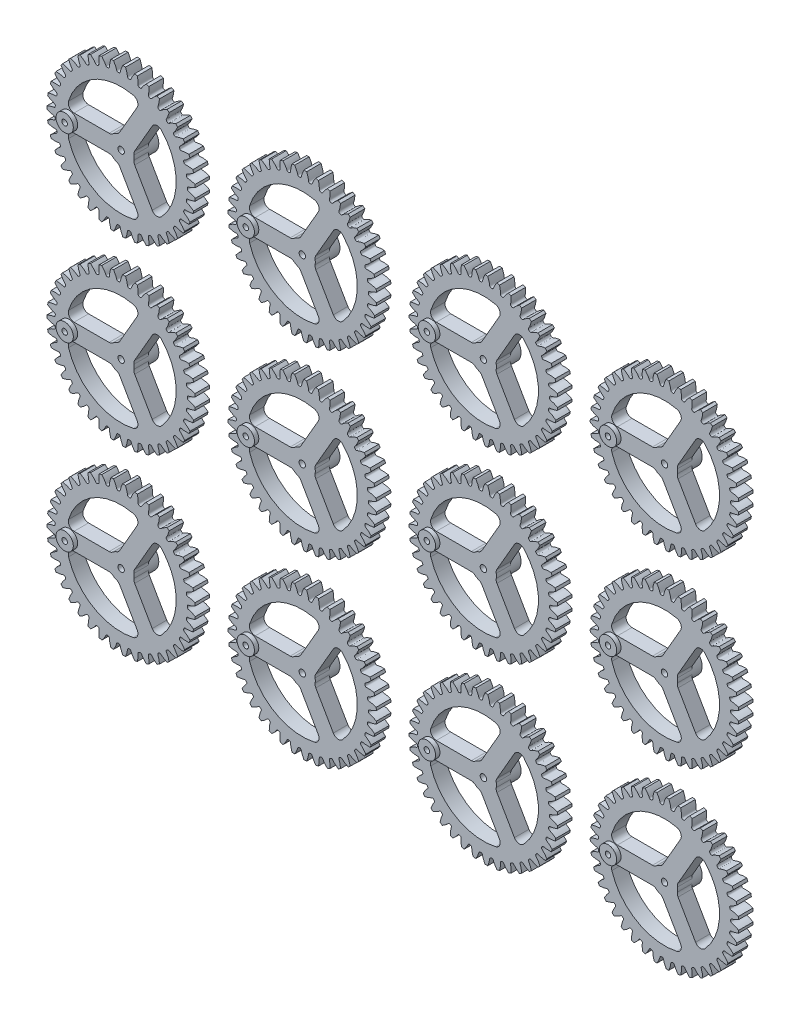
SolidWorks part; units mm, degrees
ref_plane "前视基准面" through (0, 0, 0) normal (0, 0, 1) x (1, 0, 0)
ref_plane "上视基准面" through (0, 0, 0) normal (0, 1, 0) x (1, 0, 0)
ref_plane "右视基准面" through (0, 0, 0) normal (1, 0, 0) x (0, 0, -1)
ref_axis "基准轴1" through (0, 0, 55) along (0, 0, -1)
sketch "SketchRevolveSpurGear2" plane through (0, 0, 0) normal (1, 0, 0) x (0, 0, -1)
  line L0 (0, 0) -> (1, 0) construction
  line L1 (-9.525, 0) -> (-9.525, 51.25)
  line L2 (-9.525, 51.25) -> (9.525, 51.25)
  line L3 (9.525, 51.25) -> (9.525, 0)
  line L4 (9.525, 0) -> (-9.525, 0)
revolve "SpurGear2" add sketch "SketchRevolveSpurGear2" angle 360 about L0
sketch "SketchToothSpurGear2" plane through (0, 0, 0) normal (0, 0, 1) x (1, 0, 0)
  arc A0 (51.2722, 3.2486) -> (51.2722, -3.2486) centre (0, 0) cw
  spline S0 degree 3 poles (51.2722, -3.2486) (50.9433, -3.0545) (50.5063, -2.811) (49.96, -2.5317) (49.6539, -2.3818) (49.3578, -2.2431) (49.0718, -2.1151) (48.7963, -1.9975) (48.5315, -1.8899) (48.2776, -1.7918) (48.035, -1.7028) (47.8039, -1.6225) (47.5844, -1.5505) (47.3768, -1.4864) (47.1813, -1.4298) (46.8338, -1.3346) (46.4965, -1.2659) (46.1788, -1.1645) (46.0425, -1.0887) (45.92, -0.9926) (45.8151, -0.8774) (45.7306, -0.7465) (45.6691, -0.6035) (45.6309, -0.4523) (45.6199, -0.2495) (45.6283, 0) (45.6199, 0.2495) (45.6309, 0.4523) (45.6691, 0.6035) (45.7306, 0.7465) (45.8151, 0.8774) (45.92, 0.9926) (46.0425, 1.0887) (46.1788, 1.1645) (46.4965, 1.2659) (46.8338, 1.3346) (47.1813, 1.4298) (47.3768, 1.4864) (47.5844, 1.5505) (47.8039, 1.6225) (48.035, 1.7028) (48.2776, 1.7918) (48.5315, 1.8899) (48.7963, 1.9975) (49.0718, 2.1151) (49.3578, 2.2431) (49.6539, 2.3818) (49.96, 2.5317) (50.5063, 2.811) (50.9433, 3.0545) (51.2722, 3.2486) knots 0 0 0 0 0.08292 0.108574 0.133236 0.156904 0.179579 0.201262 0.221951 0.241647 0.26035 0.27806 0.294777 0.310501 0.325231 0.338969 0.388722 0.399945 0.411168 0.422391 0.433614 0.444836 0.456059 0.467282 0.478505 0.5 0.521495 0.532718 0.543941 0.555164 0.566386 0.577609 0.588832 0.600055 0.611278 0.661031 0.674769 0.689499 0.705223 0.72194 0.73965 0.758353 0.778049 0.798738 0.820421 0.843096 0.866764 0.891426 0.91708 1 1 1 1
extrude "ToothExtrudeCutSpurGear2" cut sketch "SketchToothSpurGear2" against normal blind 9.525 and the other way blind 9.525
pattern_circular "PatternSpurGear2" count 39 every 9.231 about axis through (0, 0, 55) along (0, 0, -1) of "ToothExtrudeCutSpurGear2"
sketch "BoreRevolveSketch" plane through (0, 0, 0) normal (1, 0, 0) x (0, 0, -1)
  line L0 (0, 0) -> (1, 0) construction
  line L1 (-9.525, 0) -> (9.525, 0)
  line L2 (9.525, 0) -> (9.525, 1.5)
  line L3 (9.525, 1.5) -> (-9.525, 1.5)
  line L4 (-9.525, 1.5) -> (-9.525, 0)
  dimension "TaperSide1" = 1.5
  dimension "TaperSide2" = 1.5
revolve "BoreRevolveCut" cut sketch "BoreRevolveSketch" angle 360 about L0
sketch "AuxiliarySketchSpurGear2" plane through (0, 0, 0) normal (0, 0, 1) x (1, 0, 0)
  circle A0 centre (0, 0) radius 48.75 construction
  circle A1 centre (0, 0) radius 45.81 construction
  circle A2 centre (0, 0) radius 46.7525 construction
  circle A3 centre (0, 0) radius 51.25 construction
  circle A4 centre (0, 0) radius 45.625 construction
  dimension "PitchDiameter" = 97.5
  dimension "BaseDiameter" = 91.62
  dimension "FormDiameter" = 93.505
  dimension "MajorDiameter" = 102.5
  dimension "MinorDiameter" = 91.25
scale "缩放比例1" scale about origin uniform scaling yes scale factor 0.2
sketch "草图5" plane through (0, 0, 1.905) normal (0, 0, 1) x (1, 0, 0)
  arc A39 (0.2231, -10.2476) -> (0.6022, -10.2323) centre (0, 0) ccw
  arc A40 (1.8641, -10.0791) -> (2.2358, -10.0032) centre (0, 0) ccw
  arc A41 (3.4567, -9.6495) -> (3.8114, -9.515) centre (0, 0) ccw
  arc A42 (4.9598, -8.9701) -> (5.2884, -8.7804) centre (0, 0) ccw
  arc A43 (6.3345, -8.0583) -> (6.6284, -7.8184) centre (0, 0) ccw
  arc A44 (7.5451, -6.9378) -> (7.7967, -6.6539) centre (0, 0) ccw
  arc A45 (8.5603, -5.6377) -> (8.7631, -5.317) centre (0, 0) ccw
  arc A46 (9.3538, -4.1915) -> (9.5025, -3.8425) centre (0, 0) ccw
  arc A47 (9.9051, -2.6367) -> (9.9958, -2.2684) centre (0, 0) ccw
  arc A48 (10.1997, -1.0137) -> (10.2303, -0.6356) centre (0, 0) ccw
  arc A49 (10.2303, 0.6356) -> (10.1997, 1.0137) centre (0, 0) ccw
  arc A50 (9.9958, 2.2684) -> (9.9051, 2.6367) centre (0, 0) ccw
  arc A51 (9.5025, 3.8425) -> (9.3538, 4.1915) centre (0, 0) ccw
  arc A52 (8.7631, 5.317) -> (8.5603, 5.6377) centre (0, 0) ccw
  arc A53 (7.7967, 6.6539) -> (7.5451, 6.9378) centre (0, 0) ccw
  arc A54 (6.6284, 7.8184) -> (6.3345, 8.0583) centre (0, 0) ccw
  arc A55 (5.2884, 8.7804) -> (4.9598, 8.9701) centre (0, 0) ccw
  arc A56 (3.8114, 9.515) -> (3.4567, 9.6495) centre (0, 0) ccw
  arc A57 (2.2358, 10.0032) -> (1.8641, 10.0791) centre (0, 0) ccw
  arc A58 (0.6022, 10.2323) -> (0.2231, 10.2476) centre (0, 0) ccw
  arc A59 (-1.047, 10.1964) -> (-1.4236, 10.1507) centre (0, 0) ccw
  arc A60 (-2.669, 9.8964) -> (-3.0334, 9.7908) centre (0, 0) ccw
  arc A61 (-4.222, 9.3401) -> (-4.5647, 9.1775) centre (0, 0) ccw
  arc A62 (-5.6656, 8.5419) -> (-5.9778, 8.3264) centre (0, 0) ccw
  arc A63 (-6.9624, 7.5225) -> (-7.236, 7.2597) centre (0, 0) ccw
  arc A64 (-8.0789, 6.3082) -> (-8.3068, 6.0049) centre (0, 0) ccw
  arc A65 (-8.9862, 4.9306) -> (-9.1625, 4.5946) centre (0, 0) ccw
  arc A66 (-9.6608, 3.4252) -> (-9.7809, 3.0654) centre (0, 0) ccw
  arc A67 (-10.0851, 1.8312) -> (-10.146, 1.4567) centre (0, 0) ccw
  arc A68 (-10.2482, 0.1897) -> (-10.2482, -0.1897) centre (0, 0) ccw
  arc A69 (-10.146, -1.4567) -> (-10.0851, -1.8312) centre (0, 0) ccw
  arc A70 (-9.7809, -3.0654) -> (-9.6608, -3.4252) centre (0, 0) ccw
  arc A71 (-9.1625, -4.5946) -> (-8.9862, -4.9306) centre (0, 0) ccw
  arc A72 (-8.3068, -6.0049) -> (-8.0789, -6.3082) centre (0, 0) ccw
  arc A73 (-7.236, -7.2597) -> (-6.9624, -7.5225) centre (0, 0) ccw
  arc A74 (-5.9778, -8.3264) -> (-5.6656, -8.5419) centre (0, 0) ccw
  arc A75 (-4.5647, -9.1775) -> (-4.222, -9.3401) centre (0, 0) ccw
  arc A76 (-3.0334, -9.7908) -> (-2.669, -9.8964) centre (0, 0) ccw
  arc A77 (-1.4236, -10.1507) -> (-1.047, -10.1964) centre (0, 0) ccw
  arc A78 (0.2231, -10.2476) -> (0.6022, -10.2323) centre (0, 0) ccw
  arc A79 (1.8641, -10.0791) -> (2.2358, -10.0032) centre (0, 0) ccw
  arc A80 (3.4567, -9.6495) -> (3.8114, -9.515) centre (0, 0) ccw
  arc A81 (4.9598, -8.9701) -> (5.2884, -8.7804) centre (0, 0) ccw
  arc A82 (6.3345, -8.0583) -> (6.6284, -7.8184) centre (0, 0) ccw
  arc A83 (7.5451, -6.9378) -> (7.7967, -6.6539) centre (0, 0) ccw
  arc A84 (8.5603, -5.6377) -> (8.7631, -5.317) centre (0, 0) ccw
  arc A85 (9.3538, -4.1915) -> (9.5025, -3.8425) centre (0, 0) ccw
  arc A86 (9.9051, -2.6367) -> (9.9958, -2.2684) centre (0, 0) ccw
  arc A87 (10.1997, -1.0137) -> (10.2303, -0.6356) centre (0, 0) ccw
  arc A88 (10.2303, 0.6356) -> (10.1997, 1.0137) centre (0, 0) ccw
  arc A89 (9.9958, 2.2684) -> (9.9051, 2.6367) centre (0, 0) ccw
  arc A90 (9.5025, 3.8425) -> (9.3538, 4.1915) centre (0, 0) ccw
  arc A91 (8.7631, 5.317) -> (8.5603, 5.6377) centre (0, 0) ccw
  arc A92 (7.7967, 6.6539) -> (7.5451, 6.9378) centre (0, 0) ccw
  arc A93 (6.6284, 7.8184) -> (6.3345, 8.0583) centre (0, 0) ccw
  arc A94 (5.2884, 8.7804) -> (4.9598, 8.9701) centre (0, 0) ccw
  arc A95 (3.8114, 9.515) -> (3.4567, 9.6495) centre (0, 0) ccw
  arc A96 (2.2358, 10.0032) -> (1.8641, 10.0791) centre (0, 0) ccw
  arc A97 (0.6022, 10.2323) -> (0.2231, 10.2476) centre (0, 0) ccw
  arc A98 (-1.047, 10.1964) -> (-1.4236, 10.1507) centre (0, 0) ccw
  arc A99 (-2.669, 9.8964) -> (-3.0334, 9.7908) centre (0, 0) ccw
  arc A100 (-4.222, 9.3401) -> (-4.5647, 9.1775) centre (0, 0) ccw
  arc A101 (-5.6656, 8.5419) -> (-5.9778, 8.3264) centre (0, 0) ccw
  arc A102 (-6.9624, 7.5225) -> (-7.236, 7.2597) centre (0, 0) ccw
  arc A103 (-8.0789, 6.3082) -> (-8.3068, 6.0049) centre (0, 0) ccw
  arc A104 (-8.9862, 4.9306) -> (-9.1625, 4.5946) centre (0, 0) ccw
  arc A105 (-9.6608, 3.4252) -> (-9.7809, 3.0654) centre (0, 0) ccw
  arc A106 (-10.0851, 1.8312) -> (-10.146, 1.4567) centre (0, 0) ccw
  arc A107 (-10.2482, 0.1897) -> (-10.2482, -0.1897) centre (0, 0) ccw
  arc A108 (-10.146, -1.4567) -> (-10.0851, -1.8312) centre (0, 0) ccw
  arc A109 (-9.7809, -3.0654) -> (-9.6608, -3.4252) centre (0, 0) ccw
  arc A110 (-9.1625, -4.5946) -> (-8.9862, -4.9306) centre (0, 0) ccw
  arc A111 (-8.3068, -6.0049) -> (-8.0789, -6.3082) centre (0, 0) ccw
  arc A112 (-7.236, -7.2597) -> (-6.9624, -7.5225) centre (0, 0) ccw
  arc A113 (-5.9778, -8.3264) -> (-5.6656, -8.5419) centre (0, 0) ccw
  arc A114 (-4.5647, -9.1775) -> (-4.222, -9.3401) centre (0, 0) ccw
  arc A115 (-3.0334, -9.7908) -> (-2.669, -9.8964) centre (0, 0) ccw
  arc A116 (-1.4236, -10.1507) -> (-1.047, -10.1964) centre (0, 0) ccw
  spline S39 degree 3 poles (3980.2031, -395.6475) (-144.7935, 26.6662) (-10.7256, -27.3956) (-0.9083, -9.9635) (-0.8758, -9.9036) (-0.8457, -9.8455) (-0.8179, -9.7894) (-0.7921, -9.7353) (-0.7685, -9.6832) (-0.7469, -9.6333) (-0.7271, -9.5855) (-0.7092, -9.54) (-0.6931, -9.4967) (-0.6786, -9.4557) (-0.6657, -9.4171) (-0.6439, -9.3484) (-0.6274, -9.2816) (-0.6046, -9.2189) (-0.5883, -9.1923) (-0.5682, -9.1685) (-0.5443, -9.1485) (-0.5175, -9.1327) (-0.4884, -9.1216) (-0.4579, -9.1151) (-0.4173, -9.1146) (-0.3675, -9.1183) (-0.3175, -9.1186) (-0.2771, -9.1224) (-0.2472, -9.1313) (-0.2191, -9.1447) (-0.1936, -9.1627) (-0.1714, -9.1845) (-0.1532, -9.2098) (-0.1392, -9.2376) (-0.1215, -9.3019) (-0.1105, -9.3699) (-0.0942, -9.4401) (-0.0845, -9.4797) (-0.0734, -9.5216) (-0.0607, -9.5661) (-0.0466, -9.6129) (-0.0307, -9.6621) (-0.0132, -9.7136) (0.0062, -9.7674) (0.0275, -9.8234) (0.0508, -9.8816) (0.0761, -9.9419) (0.1036, -10.0043) (8.4863, -28.1697) (146.4675, 14.9279) (-3999.0301, -74.089) knots -21.586296 -21.586296 -21.586296 -21.586296 0.08292 0.108574 0.133236 0.156904 0.179579 0.201262 0.221951 0.241647 0.26035 0.27806 0.294777 0.310501 0.325231 0.338969 0.388722 0.399945 0.411168 0.422391 0.433614 0.444836 0.456059 0.467282 0.478505 0.5 0.521495 0.532718 0.543941 0.555164 0.566386 0.577609 0.588832 0.600055 0.611278 0.661031 0.674769 0.689499 0.705223 0.72194 0.73965 0.758353 0.778049 0.798738 0.820421 0.843096 0.866764 0.891426 0.91708 22.586117 22.586117 22.586117 22.586117 only from (-1.047, -10.1964) to (0.2231, -10.2476)
  spline S40 degree 3 poles (3992.1269, 247.9455) (-147.196, 3.0943) (-6.1922, -28.7613) (0.7018, -9.9802) (0.7241, -9.9158) (0.7445, -9.8537) (0.763, -9.7938) (0.7798, -9.7363) (0.7947, -9.6811) (0.8081, -9.6283) (0.8199, -9.578) (0.8303, -9.5302) (0.8393, -9.4849) (0.847, -9.4421) (0.8535, -9.4019) (0.8641, -9.3306) (0.8696, -9.262) (0.882, -9.1965) (0.8938, -9.1676) (0.9099, -9.141) (0.9303, -9.1174) (0.9542, -9.0974) (0.9811, -9.0818) (1.0102, -9.0705) (1.0502, -9.0635) (1.1, -9.0591) (1.1493, -9.0514) (1.1898, -9.0487) (1.2208, -9.0527) (1.2507, -9.0614) (1.2787, -9.0751) (1.3041, -9.0931) (1.3261, -9.1151) (1.3445, -9.1403) (1.3722, -9.201) (1.394, -9.2663) (1.4213, -9.333) (1.4372, -9.3704) (1.455, -9.4101) (1.4746, -9.4519) (1.4961, -9.4959) (1.5196, -9.5419) (1.5452, -9.59) (1.5729, -9.6399) (1.6029, -9.6918) (1.6352, -9.7455) (1.6699, -9.801) (1.707, -9.8581) (12.8952, -26.4436) (142.1761, 38.2297) (-3935.359, -714.6191) knots -21.586296 -21.586296 -21.586296 -21.586296 0.08292 0.108574 0.133236 0.156904 0.179579 0.201262 0.221951 0.241647 0.26035 0.27806 0.294777 0.310501 0.325231 0.338969 0.388722 0.399945 0.411168 0.422391 0.433614 0.444836 0.456059 0.467282 0.478505 0.5 0.521495 0.532718 0.543941 0.555164 0.566386 0.577609 0.588832 0.600055 0.611278 0.661031 0.674769 0.689499 0.705223 0.72194 0.73965 0.758353 0.778049 0.798738 0.820421 0.843096 0.866764 0.891426 0.91708 22.586117 22.586117 22.586117 22.586117 only from (0.6022, -10.2323) to (1.8641, -10.0791)
  spline S41 degree 3 poles (3900.6566, 885.1169) (-145.7863, -20.5577) (-1.4983, -29.3822) (2.2936, -9.7384) (2.3054, -9.6712) (2.3155, -9.6066) (2.3242, -9.5446) (2.3315, -9.4851) (2.3374, -9.4282) (2.3421, -9.374) (2.3457, -9.3224) (2.3483, -9.2736) (2.3499, -9.2274) (2.3507, -9.184) (2.3507, -9.1433) (2.3496, -9.0712) (2.344, -9.0026) (2.3458, -8.9359) (2.3528, -8.9055) (2.3645, -8.8766) (2.3808, -8.8501) (2.4012, -8.8266) (2.4253, -8.8068) (2.4522, -8.791) (2.4905, -8.7776) (2.5389, -8.7654) (2.5864, -8.7499) (2.6259, -8.7407) (2.6571, -8.7396) (2.688, -8.7435) (2.7179, -8.7524) (2.7458, -8.7662) (2.7711, -8.7843) (2.7933, -8.8063) (2.8304, -8.8617) (2.8624, -8.9227) (2.9, -8.9841) (2.9217, -9.0186) (2.9456, -9.0549) (2.9717, -9.093) (2.9999, -9.133) (3.0305, -9.1746) (3.0635, -9.2179) (3.0989, -9.2628) (3.1369, -9.3092) (3.1773, -9.357) (3.2205, -9.4062) (3.2663, -9.4566) (16.97, -24.0326) (134.2025, 60.5413) (-3769.7641, -1336.641) knots -21.586296 -21.586296 -21.586296 -21.586296 0.08292 0.108574 0.133236 0.156904 0.179579 0.201262 0.221951 0.241647 0.26035 0.27806 0.294777 0.310501 0.325231 0.338969 0.388722 0.399945 0.411168 0.422391 0.433614 0.444836 0.456059 0.467282 0.478505 0.5 0.521495 0.532718 0.543941 0.555164 0.566386 0.577609 0.588832 0.600055 0.611278 0.661031 0.674769 0.689499 0.705223 0.72194 0.73965 0.758353 0.778049 0.798738 0.820421 0.843096 0.866764 0.891426 0.91708 22.586117 22.586117 22.586117 22.586117 only from (2.2358, -10.0032) to (3.4567, -9.6495)
  spline S42 degree 3 poles (3708.1614, 1499.3642) (-140.6007, -43.6772) (3.2343, -29.242) (3.826, -9.2443) (3.8269, -9.1762) (3.8266, -9.1108) (3.8252, -9.0481) (3.8228, -8.9883) (3.8195, -8.9312) (3.8155, -8.8769) (3.8108, -8.8254) (3.8055, -8.7768) (3.7997, -8.731) (3.7934, -8.688) (3.7869, -8.6478) (3.7743, -8.5768) (3.7578, -8.51) (3.7489, -8.4439) (3.7509, -8.4128) (3.7577, -8.3824) (3.7696, -8.3536) (3.786, -8.3271) (3.8066, -8.3037) (3.8306, -8.2838) (3.8663, -8.2645) (3.9121, -8.2446) (3.9565, -8.2217) (3.994, -8.2063) (4.0246, -8.2002) (4.0558, -8.1991) (4.0867, -8.2031) (4.1165, -8.2122) (4.1443, -8.2261) (4.1697, -8.2442) (4.2153, -8.2929) (4.2566, -8.348) (4.3036, -8.4026) (4.3306, -8.4331) (4.36, -8.4651) (4.3918, -8.4986) (4.4261, -8.5335) (4.463, -8.5697) (4.5025, -8.6071) (4.5447, -8.6457) (4.5895, -8.6854) (4.6372, -8.7261) (4.6876, -8.7678) (4.7409, -8.8102) (20.6054, -20.9992) (122.7531, 81.2849) (-3506.5344, -1924.0445) knots -21.586296 -21.586296 -21.586296 -21.586296 0.08292 0.108574 0.133236 0.156904 0.179579 0.201262 0.221951 0.241647 0.26035 0.27806 0.294777 0.310501 0.325231 0.338969 0.388722 0.399945 0.411168 0.422391 0.433614 0.444836 0.456059 0.467282 0.478505 0.5 0.521495 0.532718 0.543941 0.555164 0.566386 0.577609 0.588832 0.600055 0.611278 0.661031 0.674769 0.689499 0.705223 0.72194 0.73965 0.758353 0.778049 0.798738 0.820421 0.843096 0.866764 0.891426 0.91708 22.586117 22.586117 22.586117 22.586117 only from (3.8114, -9.515) to (4.9598, -8.9701)
  spline S43 degree 3 poles (3419.6267, 2074.7787) (-131.7736, -65.6655) (7.8832, -28.3445) (5.2594, -8.5109) (5.2493, -8.4435) (5.2385, -8.379) (5.227, -8.3174) (5.2151, -8.2587) (5.2027, -8.2028) (5.19, -8.1499) (5.1771, -8.0999) (5.1641, -8.0527) (5.151, -8.0084) (5.138, -7.9669) (5.1251, -7.9283) (5.1013, -7.8603) (5.0742, -7.797) (5.0548, -7.7332) (5.0518, -7.7021) (5.0537, -7.6711) (5.0608, -7.6407) (5.0727, -7.6119) (5.0893, -7.5856) (5.1098, -7.5621) (5.1419, -7.5372) (5.184, -7.5103) (5.2241, -7.4805) (5.2587, -7.4593) (5.2879, -7.4484) (5.3185, -7.4423) (5.3496, -7.4413) (5.3805, -7.4455) (5.4102, -7.4548) (5.4382, -7.4686) (5.491, -7.5093) (5.5406, -7.5571) (5.5957, -7.6035) (5.6273, -7.6292) (5.6614, -7.6561) (5.6982, -7.684) (5.7377, -7.713) (5.7799, -7.7428) (5.8249, -7.7734) (5.8727, -7.8048) (5.9233, -7.8368) (5.9769, -7.8693) (6.0334, -7.9023) (6.0928, -7.9356) (23.707, -17.4219) (108.1245, 99.9232) (-3152.4872, -2461.6163) knots -21.586296 -21.586296 -21.586296 -21.586296 0.08292 0.108574 0.133236 0.156904 0.179579 0.201262 0.221951 0.241647 0.26035 0.27806 0.294777 0.310501 0.325231 0.338969 0.388722 0.399945 0.411168 0.422391 0.433614 0.444836 0.456059 0.467282 0.478505 0.5 0.521495 0.532718 0.543941 0.555164 0.566386 0.577609 0.588832 0.600055 0.611278 0.661031 0.674769 0.689499 0.705223 0.72194 0.73965 0.758353 0.778049 0.798738 0.820421 0.843096 0.866764 0.891426 0.91708 22.586117 22.586117 22.586117 22.586117 only from (5.2884, -8.7804) to (6.3345, -8.0583)
  spline S44 degree 3 poles (3042.5256, 2596.4576) (-119.5337, -85.9532) (12.3279, -26.7129) (6.5565, -7.557) (6.5357, -7.4921) (6.5147, -7.4302) (6.4936, -7.3712) (6.4723, -7.3151) (6.4512, -7.262) (6.4302, -7.2118) (6.4094, -7.1645) (6.3889, -7.12) (6.3689, -7.0784) (6.3494, -7.0396) (6.3305, -7.0035) (6.2961, -6.9402) (6.2593, -6.8821) (6.2299, -6.8222) (6.2219, -6.792) (6.2188, -6.761) (6.2209, -6.73) (6.2281, -6.6996) (6.2402, -6.6709) (6.2567, -6.6445) (6.2844, -6.6148) (6.3216, -6.5815) (6.3564, -6.5457) (6.3872, -6.5192) (6.4143, -6.5037) (6.4434, -6.4928) (6.474, -6.4868) (6.5052, -6.486) (6.536, -6.4904) (6.5658, -6.4995) (6.6244, -6.5313) (6.6811, -6.5704) (6.743, -6.6074) (6.7782, -6.6277) (6.8162, -6.6488) (6.857, -6.6705) (6.9006, -6.6927) (6.9471, -6.7153) (6.9964, -6.7384) (7.0486, -6.7617) (7.1037, -6.7851) (7.1618, -6.8086) (7.2229, -6.8321) (7.2869, -6.8555) (26.1947, -13.3934) (90.6955, 115.9736) (-2716.7923, -2935.4335) knots -21.586296 -21.586296 -21.586296 -21.586296 0.08292 0.108574 0.133236 0.156904 0.179579 0.201262 0.221951 0.241647 0.26035 0.27806 0.294777 0.310501 0.325231 0.338969 0.388722 0.399945 0.411168 0.422391 0.433614 0.444836 0.456059 0.467282 0.478505 0.5 0.521495 0.532718 0.543941 0.555164 0.566386 0.577609 0.588832 0.600055 0.611278 0.661031 0.674769 0.689499 0.705223 0.72194 0.73965 0.758353 0.778049 0.798738 0.820421 0.843096 0.866764 0.891426 0.91708 22.586117 22.586117 22.586117 22.586117 only from (6.6284, -7.8184) to (7.5451, -6.9378)
  spline S45 degree 3 poles (2586.6246, 3050.8896) (-104.1979, -104.0146) (16.4533, -24.3895) (7.6839, -6.4074) (7.6529, -6.3467) (7.6222, -6.2889) (7.5919, -6.2341) (7.562, -6.1822) (7.5326, -6.1332) (7.5038, -6.087) (7.4757, -6.0436) (7.4483, -6.003) (7.4219, -5.9651) (7.3964, -5.9299) (7.372, -5.8974) (7.3278, -5.8404) (7.2822, -5.7889) (7.2435, -5.7345) (7.2309, -5.706) (7.2228, -5.6759) (7.2199, -5.6449) (7.2221, -5.6138) (7.2295, -5.5836) (7.2415, -5.5548) (7.2641, -5.5211) (7.2954, -5.4822) (7.3241, -5.4413) (7.3502, -5.4102) (7.3745, -5.3906) (7.4015, -5.3751) (7.4307, -5.3643) (7.4613, -5.3585) (7.4925, -5.3579) (7.5234, -5.3621) (7.5864, -5.3841) (7.6485, -5.4136) (7.7155, -5.4402) (7.7536, -5.4546) (7.7945, -5.4693) (7.8382, -5.4841) (7.8848, -5.4991) (7.9343, -5.514) (7.9867, -5.5288) (8.042, -5.5434) (8.1002, -5.5577) (8.1613, -5.5716) (8.2253, -5.585) (8.2922, -5.5978) (28.004, -9.0181) (70.9175, 129.0204) (-2210.7339, -3333.2246) knots -21.586296 -21.586296 -21.586296 -21.586296 0.08292 0.108574 0.133236 0.156904 0.179579 0.201262 0.221951 0.241647 0.26035 0.27806 0.294777 0.310501 0.325231 0.338969 0.388722 0.399945 0.411168 0.422391 0.433614 0.444836 0.456059 0.467282 0.478505 0.5 0.521495 0.532718 0.543941 0.555164 0.566386 0.577609 0.588832 0.600055 0.611278 0.661031 0.674769 0.689499 0.705223 0.72194 0.73965 0.758353 0.778049 0.798738 0.820421 0.843096 0.866764 0.891426 0.91708 22.586117 22.586117 22.586117 22.586117 only from (7.7967, -6.6539) to (8.5603, -5.6377)
  spline S46 degree 3 poles (2063.7314, 3426.3051) (-86.1635, -119.3822) (20.1526, -21.4343) (8.6122, -5.0918) (8.5719, -5.0369) (8.5323, -4.9848) (8.4936, -4.9355) (8.4557, -4.8891) (8.4188, -4.8454) (8.383, -4.8045) (8.3483, -4.7661) (8.3148, -4.7304) (8.2827, -4.6973) (8.2519, -4.6666) (8.2225, -4.6385) (8.1698, -4.5893) (8.1165, -4.5458) (8.0696, -4.4983) (8.0525, -4.4722) (8.0398, -4.4438) (8.0319, -4.4136) (8.0291, -4.3826) (8.0315, -4.3516) (8.0388, -4.3212) (8.0557, -4.2843) (8.0804, -4.2409) (8.1021, -4.1959) (8.1229, -4.1611) (8.1437, -4.1378) (8.1679, -4.1182) (8.195, -4.1029) (8.2243, -4.0922) (8.2549, -4.0866) (8.2861, -4.0858) (8.3518, -4.0974) (8.4179, -4.1166) (8.4883, -4.1321) (8.5282, -4.1402) (8.5709, -4.1481) (8.6164, -4.1558) (8.6648, -4.163) (8.7161, -4.1698) (8.7702, -4.1761) (8.8271, -4.1816) (8.8868, -4.1864) (8.9493, -4.1903) (9.0147, -4.1933) (9.0828, -4.1952) (29.0879, -4.4091) (49.3029, 138.7256) (-1647.4187, -3644.6869) knots -21.586296 -21.586296 -21.586296 -21.586296 0.08292 0.108574 0.133236 0.156904 0.179579 0.201262 0.221951 0.241647 0.26035 0.27806 0.294777 0.310501 0.325231 0.338969 0.388722 0.399945 0.411168 0.422391 0.433614 0.444836 0.456059 0.467282 0.478505 0.5 0.521495 0.532718 0.543941 0.555164 0.566386 0.577609 0.588832 0.600055 0.611278 0.661031 0.674769 0.689499 0.705223 0.72194 0.73965 0.758353 0.778049 0.798738 0.820421 0.843096 0.866764 0.891426 0.91708 22.586117 22.586117 22.586117 22.586117 only from (8.7631, -5.317) to (9.3538, -4.1915)
  spline S47 degree 3 poles (1487.3886, 3712.9812) (-65.8974, -131.6578) (23.3299, -17.9241) (9.3174, -3.6444) (9.2689, -3.5966) (9.2215, -3.5515) (9.1753, -3.5092) (9.1305, -3.4694) (9.0871, -3.4322) (9.0451, -3.3975) (9.0047, -3.3653) (8.966, -3.3354) (8.9289, -3.3078) (8.8936, -3.2825) (8.8601, -3.2594) (8.8002, -3.2193) (8.7405, -3.1849) (8.6867, -3.1456) (8.6656, -3.1226) (8.6485, -3.0966) (8.6359, -3.0681) (8.6281, -3.0379) (8.6255, -3.0069) (8.6279, -2.9758) (8.6386, -2.9366) (8.656, -2.8898) (8.6702, -2.8419) (8.6852, -2.8042) (8.702, -2.7779) (8.7227, -2.7547) (8.747, -2.7352) (8.7742, -2.72) (8.8035, -2.7095) (8.8342, -2.7037) (8.9009, -2.7046) (8.9692, -2.713) (9.0412, -2.7169) (9.0819, -2.7186) (9.1253, -2.7195) (9.1715, -2.7198) (9.2204, -2.7192) (9.2721, -2.7177) (9.3265, -2.7151) (9.3835, -2.7115) (9.4432, -2.7066) (9.5056, -2.7005) (9.5706, -2.6929) (9.6381, -2.6839) (29.4185, 0.314) (26.4113, 144.8379) (-1041.4362, -3861.7537) knots -21.586296 -21.586296 -21.586296 -21.586296 0.08292 0.108574 0.133236 0.156904 0.179579 0.201262 0.221951 0.241647 0.26035 0.27806 0.294777 0.310501 0.325231 0.338969 0.388722 0.399945 0.411168 0.422391 0.433614 0.444836 0.456059 0.467282 0.478505 0.5 0.521495 0.532718 0.543941 0.555164 0.566386 0.577609 0.588832 0.600055 0.611278 0.661031 0.674769 0.689499 0.705223 0.72194 0.73965 0.758353 0.778049 0.798738 0.820421 0.843096 0.866764 0.891426 0.91708 22.586117 22.586117 22.586117 22.586117 only from (9.5025, -3.8425) to (9.9051, -2.6367)
  spline S48 degree 3 poles (872.5232, 3903.4929) (-43.9247, -140.5236) (25.903, -13.9496) (9.7814, -2.1026) (9.7258, -2.0632) (9.6718, -2.0263) (9.6194, -1.9919) (9.5688, -1.9598) (9.52, -1.9301) (9.473, -1.9026) (9.428, -1.8772) (9.3849, -1.854) (9.3439, -1.8327) (9.305, -1.8134) (9.2682, -1.7959) (9.2027, -1.766) (9.1383, -1.7416) (9.0788, -1.7114) (9.0543, -1.6921) (9.0332, -1.6692) (9.0162, -1.6431) (9.0037, -1.6145) (8.9962, -1.5843) (8.9935, -1.5532) (8.9978, -1.5129) (9.0075, -1.4639) (9.0138, -1.4143) (9.0225, -1.3747) (9.0349, -1.346) (9.0516, -1.3198) (9.0725, -1.2966) (9.0969, -1.2773) (9.1242, -1.2622) (9.1535, -1.2516) (9.2195, -1.2418) (9.2883, -1.2391) (9.3599, -1.2314) (9.4003, -1.2265) (9.4434, -1.2205) (9.489, -1.2134) (9.5372, -1.2049) (9.588, -1.1951) (9.6412, -1.1839) (9.697, -1.1712) (9.7551, -1.1568) (9.8157, -1.1407) (9.8786, -1.1228) (9.9438, -1.1031) (28.9872, 5.029) (2.8356, 147.1989) (-408.481, -3978.8031) knots -21.586296 -21.586296 -21.586296 -21.586296 0.08292 0.108574 0.133236 0.156904 0.179579 0.201262 0.221951 0.241647 0.26035 0.27806 0.294777 0.310501 0.325231 0.338969 0.388722 0.399945 0.411168 0.422391 0.433614 0.444836 0.456059 0.467282 0.478505 0.5 0.521495 0.532718 0.543941 0.555164 0.566386 0.577609 0.588832 0.600055 0.611278 0.661031 0.674769 0.689499 0.705223 0.72194 0.73965 0.758353 0.778049 0.798738 0.820421 0.843096 0.866764 0.891426 0.91708 22.586117 22.586117 22.586117 22.586117 only from (9.9958, -2.2684) to (10.1997, -1.0137)
  spline S49 degree 3 poles (235.06, 3992.9063) (-20.8143, -145.7498) (27.8052, -9.6138) (9.992, -0.5063) (9.9308, -0.4764) (9.8716, -0.4486) (9.8144, -0.423) (9.7593, -0.3995) (9.7063, -0.378) (9.6555, -0.3584) (9.607, -0.3406) (9.5608, -0.3245) (9.5169, -0.3101) (9.4754, -0.2973) (9.4363, -0.286) (9.3668, -0.2669) (9.2993, -0.2532) (9.2358, -0.2329) (9.2085, -0.2177) (9.184, -0.1985) (9.163, -0.1755) (9.1461, -0.1493) (9.1338, -0.1207) (9.1262, -0.0905) (9.124, -0.0499) (9.1257, 0) (9.124, 0.0499) (9.1262, 0.0905) (9.1338, 0.1207) (9.1461, 0.1493) (9.163, 0.1755) (9.184, 0.1985) (9.2085, 0.2177) (9.2358, 0.2329) (9.2993, 0.2532) (9.3668, 0.2669) (9.4363, 0.286) (9.4754, 0.2973) (9.5169, 0.3101) (9.5608, 0.3245) (9.607, 0.3406) (9.6555, 0.3584) (9.7063, 0.378) (9.7593, 0.3995) (9.8144, 0.423) (9.8716, 0.4486) (9.9308, 0.4764) (9.992, 0.5063) (27.8051, 9.6137) (-20.8135, 145.7476) (235.0536, -3992.8036) knots -21.586296 -21.586296 -21.586296 -21.586296 0.08292 0.108574 0.133236 0.156904 0.179579 0.201262 0.221951 0.241647 0.26035 0.27806 0.294777 0.310501 0.325231 0.338969 0.388722 0.399945 0.411168 0.422391 0.433614 0.444836 0.456059 0.467282 0.478505 0.5 0.521495 0.532718 0.543941 0.555164 0.566386 0.577609 0.588832 0.600055 0.611278 0.661031 0.674769 0.689499 0.705223 0.72194 0.73965 0.758353 0.778049 0.798738 0.820421 0.843096 0.866764 0.891426 0.91708 22.586117 22.586117 22.586117 22.586117 only from (10.2303, -0.6356) to (10.2303, 0.6356)
  spline S50 degree 3 poles (-408.4912, 3978.9055) (2.8352, -147.2013) (28.9873, -5.029) (9.9438, 1.1031) (9.8786, 1.1228) (9.8157, 1.1407) (9.7551, 1.1568) (9.697, 1.1712) (9.6412, 1.1839) (9.588, 1.1951) (9.5372, 1.2049) (9.489, 1.2134) (9.4434, 1.2205) (9.4003, 1.2265) (9.3599, 1.2314) (9.2883, 1.2391) (9.2195, 1.2418) (9.1535, 1.2516) (9.1242, 1.2622) (9.0969, 1.2773) (9.0725, 1.2966) (9.0516, 1.3198) (9.0349, 1.346) (9.0225, 1.3747) (9.0138, 1.4143) (9.0075, 1.4639) (8.9978, 1.5129) (8.9935, 1.5532) (8.9962, 1.5843) (9.0037, 1.6145) (9.0162, 1.6431) (9.0332, 1.6692) (9.0543, 1.6921) (9.0788, 1.7114) (9.1383, 1.7416) (9.2027, 1.766) (9.2682, 1.7959) (9.305, 1.8134) (9.3439, 1.8327) (9.3849, 1.854) (9.428, 1.8772) (9.473, 1.9026) (9.52, 1.9301) (9.5688, 1.9598) (9.6194, 1.9919) (9.6718, 2.0263) (9.7258, 2.0632) (9.7814, 2.1026) (25.9029, 13.9495) (-43.9235, 140.5215) (872.5005, -3903.3926) knots -21.586296 -21.586296 -21.586296 -21.586296 0.08292 0.108574 0.133236 0.156904 0.179579 0.201262 0.221951 0.241647 0.26035 0.27806 0.294777 0.310501 0.325231 0.338969 0.388722 0.399945 0.411168 0.422391 0.433614 0.444836 0.456059 0.467282 0.478505 0.5 0.521495 0.532718 0.543941 0.555164 0.566386 0.577609 0.588832 0.600055 0.611278 0.661031 0.674769 0.689499 0.705223 0.72194 0.73965 0.758353 0.778049 0.798738 0.820421 0.843096 0.866764 0.891426 0.91708 22.586117 22.586117 22.586117 22.586117 only from (10.1997, 1.0137) to (9.9958, 2.2684)
  spline S51 degree 3 poles (-1041.4627, 3861.8531) (26.4112, -144.8403) (29.4187, -0.314) (9.6381, 2.6839) (9.5706, 2.6929) (9.5056, 2.7005) (9.4432, 2.7066) (9.3835, 2.7115) (9.3265, 2.7151) (9.2721, 2.7177) (9.2204, 2.7192) (9.1715, 2.7198) (9.1253, 2.7195) (9.0819, 2.7186) (9.0412, 2.7169) (8.9692, 2.713) (8.9009, 2.7046) (8.8342, 2.7037) (8.8035, 2.7095) (8.7742, 2.72) (8.747, 2.7352) (8.7227, 2.7547) (8.702, 2.7779) (8.6852, 2.8042) (8.6702, 2.8419) (8.656, 2.8898) (8.6386, 2.9366) (8.6279, 2.9758) (8.6255, 3.0069) (8.6281, 3.0379) (8.6359, 3.0681) (8.6485, 3.0966) (8.6656, 3.1226) (8.6867, 3.1456) (8.7405, 3.1849) (8.8002, 3.2193) (8.8601, 3.2594) (8.8936, 3.2825) (8.9289, 3.3078) (8.966, 3.3354) (9.0047, 3.3653) (9.0451, 3.3975) (9.0871, 3.4322) (9.1305, 3.4694) (9.1753, 3.5092) (9.2215, 3.5515) (9.2689, 3.5966) (9.3174, 3.6444) (23.3298, 17.924) (-65.8959, 131.6559) (1487.35, -3712.8857) knots -21.586296 -21.586296 -21.586296 -21.586296 0.08292 0.108574 0.133236 0.156904 0.179579 0.201262 0.221951 0.241647 0.26035 0.27806 0.294777 0.310501 0.325231 0.338969 0.388722 0.399945 0.411168 0.422391 0.433614 0.444836 0.456059 0.467282 0.478505 0.5 0.521495 0.532718 0.543941 0.555164 0.566386 0.577609 0.588832 0.600055 0.611278 0.661031 0.674769 0.689499 0.705223 0.72194 0.73965 0.758353 0.778049 0.798738 0.820421 0.843096 0.866764 0.891426 0.91708 22.586117 22.586117 22.586117 22.586117 only from (9.9051, 2.6367) to (9.5025, 3.8425)
  spline S52 degree 3 poles (-1647.4608, 3644.7808) (49.3032, -138.728) (29.0881, 4.4091) (9.0828, 4.1952) (9.0147, 4.1933) (8.9493, 4.1903) (8.8868, 4.1864) (8.8271, 4.1816) (8.7702, 4.1761) (8.7161, 4.1698) (8.6648, 4.163) (8.6164, 4.1558) (8.5709, 4.1481) (8.5282, 4.1402) (8.4883, 4.1321) (8.4179, 4.1166) (8.3518, 4.0974) (8.2861, 4.0858) (8.2549, 4.0866) (8.2243, 4.0922) (8.195, 4.1029) (8.1679, 4.1182) (8.1437, 4.1378) (8.1229, 4.1611) (8.1021, 4.1959) (8.0804, 4.2409) (8.0557, 4.2843) (8.0388, 4.3212) (8.0315, 4.3516) (8.0291, 4.3826) (8.0319, 4.4136) (8.0398, 4.4438) (8.0525, 4.4722) (8.0696, 4.4983) (8.1165, 4.5458) (8.1698, 4.5893) (8.2225, 4.6385) (8.2519, 4.6666) (8.2827, 4.6973) (8.3148, 4.7304) (8.3483, 4.7661) (8.383, 4.8045) (8.4188, 4.8454) (8.4557, 4.8891) (8.4936, 4.9355) (8.5323, 4.9848) (8.5719, 5.0369) (8.6122, 5.0918) (20.1525, 21.4342) (-86.1617, 119.3806) (2063.678, -3426.2171) knots -21.586296 -21.586296 -21.586296 -21.586296 0.08292 0.108574 0.133236 0.156904 0.179579 0.201262 0.221951 0.241647 0.26035 0.27806 0.294777 0.310501 0.325231 0.338969 0.388722 0.399945 0.411168 0.422391 0.433614 0.444836 0.456059 0.467282 0.478505 0.5 0.521495 0.532718 0.543941 0.555164 0.566386 0.577609 0.588832 0.600055 0.611278 0.661031 0.674769 0.689499 0.705223 0.72194 0.73965 0.758353 0.778049 0.798738 0.820421 0.843096 0.866764 0.891426 0.91708 22.586117 22.586117 22.586117 22.586117 only from (9.3538, 4.1915) to (8.7631, 5.317)
  spline S53 degree 3 poles (-2210.7906, 3333.3105) (70.9183, -129.0227) (28.0041, 9.0181) (8.2922, 5.5978) (8.2253, 5.585) (8.1613, 5.5716) (8.1002, 5.5577) (8.042, 5.5434) (7.9867, 5.5288) (7.9343, 5.514) (7.8848, 5.4991) (7.8382, 5.4841) (7.7945, 5.4693) (7.7536, 5.4546) (7.7155, 5.4402) (7.6485, 5.4136) (7.5864, 5.3841) (7.5234, 5.3621) (7.4925, 5.3579) (7.4613, 5.3585) (7.4307, 5.3643) (7.4015, 5.3751) (7.3745, 5.3906) (7.3502, 5.4102) (7.3241, 5.4413) (7.2954, 5.4822) (7.2641, 5.5211) (7.2415, 5.5548) (7.2295, 5.5836) (7.2221, 5.6138) (7.2199, 5.6449) (7.2228, 5.6759) (7.2309, 5.706) (7.2435, 5.7345) (7.2822, 5.7889) (7.3278, 5.8404) (7.372, 5.8974) (7.3964, 5.9299) (7.4219, 5.9651) (7.4483, 6.003) (7.4757, 6.0436) (7.5038, 6.087) (7.5326, 6.1332) (7.562, 6.1822) (7.5919, 6.2341) (7.6222, 6.2889) (7.6529, 6.3467) (7.6839, 6.4074) (16.4532, 24.3893) (-104.1959, 104.0133) (2586.5578, -3050.8113) knots -21.586296 -21.586296 -21.586296 -21.586296 0.08292 0.108574 0.133236 0.156904 0.179579 0.201262 0.221951 0.241647 0.26035 0.27806 0.294777 0.310501 0.325231 0.338969 0.388722 0.399945 0.411168 0.422391 0.433614 0.444836 0.456059 0.467282 0.478505 0.5 0.521495 0.532718 0.543941 0.555164 0.566386 0.577609 0.588832 0.600055 0.611278 0.661031 0.674769 0.689499 0.705223 0.72194 0.73965 0.758353 0.778049 0.798738 0.820421 0.843096 0.866764 0.891426 0.91708 22.586117 22.586117 22.586117 22.586117 only from (8.5603, 5.6377) to (7.7967, 6.6539)
  spline S54 degree 3 poles (-2716.862, 2935.5093) (90.6966, -115.9758) (26.1949, 13.3935) (7.2869, 6.8555) (7.2229, 6.8321) (7.1618, 6.8086) (7.1037, 6.7851) (7.0486, 6.7617) (6.9964, 6.7384) (6.9471, 6.7153) (6.9006, 6.6927) (6.857, 6.6705) (6.8162, 6.6488) (6.7782, 6.6277) (6.743, 6.6074) (6.6811, 6.5704) (6.6244, 6.5313) (6.5658, 6.4995) (6.536, 6.4904) (6.5052, 6.486) (6.474, 6.4868) (6.4434, 6.4928) (6.4143, 6.5037) (6.3872, 6.5192) (6.3564, 6.5457) (6.3216, 6.5815) (6.2844, 6.6148) (6.2567, 6.6445) (6.2402, 6.6709) (6.2281, 6.6996) (6.2209, 6.73) (6.2188, 6.761) (6.2219, 6.792) (6.2299, 6.8222) (6.2593, 6.8821) (6.2961, 6.9402) (6.3305, 7.0035) (6.3494, 7.0396) (6.3689, 7.0784) (6.3889, 7.12) (6.4094, 7.1645) (6.4302, 7.2118) (6.4512, 7.262) (6.4723, 7.3151) (6.4936, 7.3712) (6.5147, 7.4302) (6.5357, 7.4921) (6.5565, 7.557) (12.3278, 26.7128) (-119.5315, 85.9522) (3042.4471, -2596.391) knots -21.586296 -21.586296 -21.586296 -21.586296 0.08292 0.108574 0.133236 0.156904 0.179579 0.201262 0.221951 0.241647 0.26035 0.27806 0.294777 0.310501 0.325231 0.338969 0.388722 0.399945 0.411168 0.422391 0.433614 0.444836 0.456059 0.467282 0.478505 0.5 0.521495 0.532718 0.543941 0.555164 0.566386 0.577609 0.588832 0.600055 0.611278 0.661031 0.674769 0.689499 0.705223 0.72194 0.73965 0.758353 0.778049 0.798738 0.820421 0.843096 0.866764 0.891426 0.91708 22.586117 22.586117 22.586117 22.586117 only from (7.5451, 6.9378) to (6.6284, 7.8184)
  spline S55 degree 3 poles (-3152.5682, 2461.6799) (108.1259, -99.9252) (23.7072, 17.422) (6.0928, 7.9356) (6.0334, 7.9023) (5.9769, 7.8693) (5.9233, 7.8368) (5.8727, 7.8048) (5.8249, 7.7734) (5.7799, 7.7428) (5.7377, 7.713) (5.6982, 7.684) (5.6614, 7.6561) (5.6273, 7.6292) (5.5957, 7.6035) (5.5406, 7.5571) (5.491, 7.5093) (5.4382, 7.4686) (5.4102, 7.4548) (5.3805, 7.4455) (5.3496, 7.4413) (5.3185, 7.4423) (5.2879, 7.4484) (5.2587, 7.4593) (5.2241, 7.4805) (5.184, 7.5103) (5.1419, 7.5372) (5.1098, 7.5621) (5.0893, 7.5856) (5.0727, 7.6119) (5.0608, 7.6407) (5.0537, 7.6711) (5.0518, 7.7021) (5.0548, 7.7332) (5.0742, 7.797) (5.1013, 7.8603) (5.1251, 7.9283) (5.138, 7.9669) (5.151, 8.0084) (5.1641, 8.0527) (5.1771, 8.0999) (5.19, 8.1499) (5.2027, 8.2028) (5.2151, 8.2587) (5.227, 8.3174) (5.2385, 8.379) (5.2493, 8.4435) (5.2594, 8.5109) (7.8832, 28.3444) (-131.7713, 65.6649) (3419.5386, -2074.7256) knots -21.586296 -21.586296 -21.586296 -21.586296 0.08292 0.108574 0.133236 0.156904 0.179579 0.201262 0.221951 0.241647 0.26035 0.27806 0.294777 0.310501 0.325231 0.338969 0.388722 0.399945 0.411168 0.422391 0.433614 0.444836 0.456059 0.467282 0.478505 0.5 0.521495 0.532718 0.543941 0.555164 0.566386 0.577609 0.588832 0.600055 0.611278 0.661031 0.674769 0.689499 0.705223 0.72194 0.73965 0.758353 0.778049 0.798738 0.820421 0.843096 0.866764 0.891426 0.91708 22.586117 22.586117 22.586117 22.586117 only from (6.3345, 8.0583) to (5.2884, 8.7804)
  spline S56 degree 3 poles (-3506.6245, 1924.0943) (122.7548, -81.2865) (20.6055, 20.9993) (4.7409, 8.8102) (4.6876, 8.7678) (4.6372, 8.7261) (4.5895, 8.6854) (4.5447, 8.6457) (4.5025, 8.6071) (4.463, 8.5697) (4.4261, 8.5335) (4.3918, 8.4986) (4.36, 8.4651) (4.3306, 8.4331) (4.3036, 8.4026) (4.2566, 8.348) (4.2153, 8.2929) (4.1697, 8.2442) (4.1443, 8.2261) (4.1165, 8.2122) (4.0867, 8.2031) (4.0558, 8.1991) (4.0246, 8.2002) (3.994, 8.2063) (3.9565, 8.2217) (3.9121, 8.2446) (3.8663, 8.2645) (3.8306, 8.2838) (3.8066, 8.3037) (3.786, 8.3271) (3.7696, 8.3536) (3.7577, 8.3824) (3.7509, 8.4128) (3.7489, 8.4439) (3.7578, 8.51) (3.7743, 8.5768) (3.7869, 8.6478) (3.7934, 8.688) (3.7997, 8.731) (3.8055, 8.7768) (3.8108, 8.8254) (3.8155, 8.8769) (3.8195, 8.9312) (3.8228, 8.9883) (3.8252, 9.0481) (3.8266, 9.1108) (3.8269, 9.1762) (3.826, 9.2443) (3.2343, 29.2419) (-140.5983, 43.677) (3708.0659, -1499.3259) knots -21.586296 -21.586296 -21.586296 -21.586296 0.08292 0.108574 0.133236 0.156904 0.179579 0.201262 0.221951 0.241647 0.26035 0.27806 0.294777 0.310501 0.325231 0.338969 0.388722 0.399945 0.411168 0.422391 0.433614 0.444836 0.456059 0.467282 0.478505 0.5 0.521495 0.532718 0.543941 0.555164 0.566386 0.577609 0.588832 0.600055 0.611278 0.661031 0.674769 0.689499 0.705223 0.72194 0.73965 0.758353 0.778049 0.798738 0.820421 0.843096 0.866764 0.891426 0.91708 22.586117 22.586117 22.586117 22.586117 only from (4.9598, 8.9701) to (3.8114, 9.515)
  spline S57 degree 3 poles (-3769.861, 1336.6756) (134.2045, -60.5426) (16.9701, 24.0327) (3.2663, 9.4566) (3.2205, 9.4062) (3.1773, 9.357) (3.1369, 9.3092) (3.0989, 9.2628) (3.0635, 9.2179) (3.0305, 9.1746) (2.9999, 9.133) (2.9717, 9.093) (2.9456, 9.0549) (2.9217, 9.0186) (2.9, 8.9841) (2.8624, 8.9227) (2.8304, 8.8617) (2.7933, 8.8063) (2.7711, 8.7843) (2.7458, 8.7662) (2.7179, 8.7524) (2.688, 8.7435) (2.6571, 8.7396) (2.6259, 8.7407) (2.5864, 8.7499) (2.5389, 8.7654) (2.4905, 8.7776) (2.4522, 8.791) (2.4253, 8.8068) (2.4012, 8.8266) (2.3808, 8.8501) (2.3645, 8.8766) (2.3528, 8.9055) (2.3458, 8.9359) (2.344, 9.0026) (2.3496, 9.0712) (2.3507, 9.1433) (2.3507, 9.184) (2.3499, 9.2274) (2.3483, 9.2736) (2.3457, 9.3224) (2.3421, 9.374) (2.3374, 9.4282) (2.3315, 9.4851) (2.3242, 9.5446) (2.3155, 9.6066) (2.3054, 9.6712) (2.2936, 9.7384) (-1.4983, 29.382) (-145.7839, 20.5578) (3900.5562, -885.0944) knots -21.586296 -21.586296 -21.586296 -21.586296 0.08292 0.108574 0.133236 0.156904 0.179579 0.201262 0.221951 0.241647 0.26035 0.27806 0.294777 0.310501 0.325231 0.338969 0.388722 0.399945 0.411168 0.422391 0.433614 0.444836 0.456059 0.467282 0.478505 0.5 0.521495 0.532718 0.543941 0.555164 0.566386 0.577609 0.588832 0.600055 0.611278 0.661031 0.674769 0.689499 0.705223 0.72194 0.73965 0.758353 0.778049 0.798738 0.820421 0.843096 0.866764 0.891426 0.91708 22.586117 22.586117 22.586117 22.586117 only from (3.4567, 9.6495) to (2.2358, 10.0032)
  spline S58 degree 3 poles (-3935.4602, 714.6378) (142.1783, -38.2307) (12.8953, 26.4437) (1.707, 9.8581) (1.6699, 9.801) (1.6352, 9.7455) (1.6029, 9.6918) (1.5729, 9.6399) (1.5452, 9.59) (1.5196, 9.5419) (1.4961, 9.4959) (1.4746, 9.4519) (1.455, 9.4101) (1.4372, 9.3704) (1.4213, 9.333) (1.394, 9.2663) (1.3722, 9.201) (1.3445, 9.1403) (1.3261, 9.1151) (1.3041, 9.0931) (1.2787, 9.0751) (1.2507, 9.0614) (1.2208, 9.0527) (1.1898, 9.0487) (1.1493, 9.0514) (1.1, 9.0591) (1.0502, 9.0635) (1.0102, 9.0705) (0.9811, 9.0818) (0.9542, 9.0974) (0.9303, 9.1174) (0.9099, 9.141) (0.8938, 9.1676) (0.882, 9.1965) (0.8696, 9.262) (0.8641, 9.3306) (0.8535, 9.4019) (0.847, 9.4421) (0.8393, 9.4849) (0.8303, 9.5302) (0.8199, 9.578) (0.8081, 9.6283) (0.7947, 9.6811) (0.7798, 9.7363) (0.763, 9.7938) (0.7445, 9.8537) (0.7241, 9.9158) (0.7018, 9.9802) (-6.1921, 28.7612) (-147.1937, -3.0938) (3992.0241, -247.9395) knots -21.586296 -21.586296 -21.586296 -21.586296 0.08292 0.108574 0.133236 0.156904 0.179579 0.201262 0.221951 0.241647 0.26035 0.27806 0.294777 0.310501 0.325231 0.338969 0.388722 0.399945 0.411168 0.422391 0.433614 0.444836 0.456059 0.467282 0.478505 0.5 0.521495 0.532718 0.543941 0.555164 0.566386 0.577609 0.588832 0.600055 0.611278 0.661031 0.674769 0.689499 0.705223 0.72194 0.73965 0.758353 0.778049 0.798738 0.820421 0.843096 0.866764 0.891426 0.91708 22.586117 22.586117 22.586117 22.586117 only from (1.8641, 10.0791) to (0.6022, 10.2323)
  spline S59 degree 3 poles (-3999.133, 74.0912) (146.4697, -14.9287) (8.4864, 28.1698) (0.1036, 10.0043) (0.0761, 9.9419) (0.0508, 9.8816) (0.0275, 9.8234) (0.0062, 9.7674) (-0.0132, 9.7136) (-0.0307, 9.6621) (-0.0466, 9.6129) (-0.0607, 9.5661) (-0.0734, 9.5216) (-0.0845, 9.4797) (-0.0942, 9.4401) (-0.1105, 9.3699) (-0.1215, 9.3019) (-0.1392, 9.2376) (-0.1532, 9.2098) (-0.1714, 9.1845) (-0.1936, 9.1627) (-0.2191, 9.1447) (-0.2472, 9.1313) (-0.2771, 9.1224) (-0.3175, 9.1186) (-0.3675, 9.1183) (-0.4173, 9.1146) (-0.4579, 9.1151) (-0.4884, 9.1216) (-0.5175, 9.1327) (-0.5443, 9.1485) (-0.5682, 9.1685) (-0.5883, 9.1923) (-0.6046, 9.2189) (-0.6274, 9.2816) (-0.6439, 9.3484) (-0.6657, 9.4171) (-0.6786, 9.4557) (-0.6931, 9.4967) (-0.7092, 9.54) (-0.7271, 9.5855) (-0.7469, 9.6333) (-0.7685, 9.6832) (-0.7921, 9.7353) (-0.8179, 9.7894) (-0.8457, 9.8455) (-0.8758, 9.9036) (-0.9083, 9.9635) (-10.7255, 27.3954) (-144.7913, -26.6653) (3980.1007, 395.637) knots -21.586296 -21.586296 -21.586296 -21.586296 0.08292 0.108574 0.133236 0.156904 0.179579 0.201262 0.221951 0.241647 0.26035 0.27806 0.294777 0.310501 0.325231 0.338969 0.388722 0.399945 0.411168 0.422391 0.433614 0.444836 0.456059 0.467282 0.478505 0.5 0.521495 0.532718 0.543941 0.555164 0.566386 0.577609 0.588832 0.600055 0.611278 0.661031 0.674769 0.689499 0.705223 0.72194 0.73965 0.758353 0.778049 0.798738 0.820421 0.843096 0.866764 0.891426 0.91708 22.586117 22.586117 22.586117 22.586117 only from (0.2231, 10.2476) to (-1.047, 10.1964)
  spline S60 degree 3 poles (-3959.2303, -568.3743) (146.9677, 8.7601) (3.8577, 29.1663) (-1.5026, 9.8913) (-1.5197, 9.8254) (-1.535, 9.7618) (-1.5486, 9.7006) (-1.5607, 9.6419) (-1.5712, 9.5857) (-1.5802, 9.5321) (-1.588, 9.481) (-1.5945, 9.4325) (-1.5998, 9.3866) (-1.6041, 9.3433) (-1.6073, 9.3028) (-1.6121, 9.2309) (-1.612, 9.162) (-1.6192, 9.0957) (-1.6286, 9.0659) (-1.6425, 9.0381) (-1.6609, 9.0129) (-1.6832, 8.9911) (-1.7087, 8.9734) (-1.7368, 8.9598) (-1.7761, 8.9496) (-1.8254, 8.9412) (-1.8739, 8.9296) (-1.9141, 8.9236) (-1.9453, 8.9251) (-1.9757, 8.9314) (-2.0048, 8.9427) (-2.0315, 8.9587) (-2.0553, 8.9788) (-2.0756, 9.0025) (-2.1082, 9.0607) (-2.1351, 9.1241) (-2.1677, 9.1884) (-2.1866, 9.2244) (-2.2075, 9.2625) (-2.2303, 9.3026) (-2.2553, 9.3447) (-2.2825, 9.3887) (-2.3118, 9.4345) (-2.3435, 9.4821) (-2.3776, 9.5314) (-2.4141, 9.5823) (-2.4531, 9.6348) (-2.4948, 9.6888) (-14.9812, 25.3202) (-138.6389, -49.5461) (3865.0949, 1028.9667) knots -21.586296 -21.586296 -21.586296 -21.586296 0.08292 0.108574 0.133236 0.156904 0.179579 0.201262 0.221951 0.241647 0.26035 0.27806 0.294777 0.310501 0.325231 0.338969 0.388722 0.399945 0.411168 0.422391 0.433614 0.444836 0.456059 0.467282 0.478505 0.5 0.521495 0.532718 0.543941 0.555164 0.566386 0.577609 0.588832 0.600055 0.611278 0.661031 0.674769 0.689499 0.705223 0.72194 0.73965 0.758353 0.778049 0.798738 0.820421 0.843096 0.866764 0.891426 0.91708 22.586117 22.586117 22.586117 22.586117 only from (-1.4236, 10.1507) to (-2.669, 9.8964)
  spline S61 degree 3 poles (-3816.7857, -1196.1192) (143.6593, 32.2219) (-0.8708, 29.4075) (-3.0698, 9.5222) (-3.0761, 9.4544) (-3.081, 9.3892) (-3.0847, 9.3266) (-3.0871, 9.2667) (-3.0885, 9.2096) (-3.0888, 9.1551) (-3.0883, 9.1035) (-3.0869, 9.0545) (-3.0848, 9.0084) (-3.0821, 8.965) (-3.0788, 8.9245) (-3.0719, 8.8527) (-3.0608, 8.7848) (-3.0573, 8.7182) (-3.0618, 8.6873) (-3.0711, 8.6576) (-3.0852, 8.6298) (-3.1037, 8.6047) (-3.126, 8.5831) (-3.1516, 8.5652) (-3.1887, 8.5488) (-3.236, 8.5326) (-3.2821, 8.5134) (-3.3208, 8.501) (-3.3518, 8.4975) (-3.3829, 8.4988) (-3.4133, 8.5054) (-3.4423, 8.5168) (-3.469, 8.5329) (-3.4928, 8.553) (-3.5343, 8.6052) (-3.5711, 8.6634) (-3.6135, 8.7217) (-3.638, 8.7542) (-3.6647, 8.7885) (-3.6937, 8.8244) (-3.7251, 8.8619) (-3.759, 8.901) (-3.7953, 8.9415) (-3.8342, 8.9834) (-3.8758, 9.0266) (-3.92, 9.071) (-3.9669, 9.1165) (-4.0166, 9.1631) (-18.8488, 22.5891) (-128.8958, -71.1438) (3649.985, 1635.6466) knots -21.586296 -21.586296 -21.586296 -21.586296 0.08292 0.108574 0.133236 0.156904 0.179579 0.201262 0.221951 0.241647 0.26035 0.27806 0.294777 0.310501 0.325231 0.338969 0.388722 0.399945 0.411168 0.422391 0.433614 0.444836 0.456059 0.467282 0.478505 0.5 0.521495 0.532718 0.543941 0.555164 0.566386 0.577609 0.588832 0.600055 0.611278 0.661031 0.674769 0.689499 0.705223 0.72194 0.73965 0.758353 0.778049 0.798738 0.820421 0.843096 0.866764 0.891426 0.91708 22.586117 22.586117 22.586117 22.586117 only from (-3.0334, 9.7908) to (-4.222, 9.3401)
  spline S62 degree 3 poles (-3575.4883, -1792.8852) (136.6302, 54.8492) (-5.5768, 28.8869) (-4.5575, 8.9065) (-4.5529, 8.8385) (-4.5473, 8.7733) (-4.5408, 8.711) (-4.5336, 8.6515) (-4.5258, 8.5949) (-4.5174, 8.5411) (-4.5086, 8.4902) (-4.4994, 8.4421) (-4.4899, 8.3969) (-4.4802, 8.3545) (-4.4705, 8.315) (-4.4522, 8.2453) (-4.4304, 8.18) (-4.4162, 8.1149) (-4.4157, 8.0837) (-4.4201, 8.0528) (-4.4295, 8.0231) (-4.4438, 7.9954) (-4.4624, 7.9705) (-4.4848, 7.9487) (-4.5188, 7.9266) (-4.5628, 7.9031) (-4.6052, 7.8766) (-4.6414, 7.8583) (-4.6714, 7.8498) (-4.7024, 7.8461) (-4.7335, 7.8477) (-4.7639, 7.8543) (-4.7928, 7.8659) (-4.8196, 7.8819) (-4.8689, 7.9268) (-4.9145, 7.9784) (-4.9658, 8.0291) (-4.9951, 8.0573) (-5.027, 8.0868) (-5.0614, 8.1176) (-5.0984, 8.1496) (-5.1381, 8.1828) (-5.1805, 8.2169) (-5.2256, 8.252) (-5.2735, 8.288) (-5.3243, 8.3247) (-5.3779, 8.3621) (-5.4345, 8.4002) (-22.2283, 19.2731) (-115.8144, -90.8988) (3340.3425, 2199.9642) knots -21.586296 -21.586296 -21.586296 -21.586296 0.08292 0.108574 0.133236 0.156904 0.179579 0.201262 0.221951 0.241647 0.26035 0.27806 0.294777 0.310501 0.325231 0.338969 0.388722 0.399945 0.411168 0.422391 0.433614 0.444836 0.456059 0.467282 0.478505 0.5 0.521495 0.532718 0.543941 0.555164 0.566386 0.577609 0.588832 0.600055 0.611278 0.661031 0.674769 0.689499 0.705223 0.72194 0.73965 0.758353 0.778049 0.798738 0.820421 0.843096 0.866764 0.891426 0.91708 22.586117 22.586117 22.586117 22.586117 only from (-4.5647, 9.1775) to (-5.6656, 8.5419)
  spline S63 degree 3 poles (-3241.5876, -2343.2165) (126.0624, 76.056) (-10.1384, 27.6183) (-5.9272, 8.0601) (-5.9117, 7.9937) (-5.8957, 7.9303) (-5.8794, 7.8698) (-5.8627, 7.8122) (-5.8459, 7.7576) (-5.829, 7.7059) (-5.8121, 7.657) (-5.7953, 7.6111) (-5.7787, 7.5679) (-5.7624, 7.5277) (-5.7464, 7.4902) (-5.7172, 7.4244) (-5.6852, 7.3634) (-5.6607, 7.3014) (-5.6552, 7.2706) (-5.6546, 7.2395) (-5.6592, 7.2087) (-5.6688, 7.1791) (-5.6832, 7.1514) (-5.7017, 7.1264) (-5.7318, 7.099) (-5.7715, 7.0688) (-5.8091, 7.0359) (-5.8419, 7.012) (-5.8701, 6.9988) (-5.9001, 6.9902) (-5.931, 6.9867) (-5.9622, 6.9884) (-5.9925, 6.9952) (-6.0215, 7.0068) (-6.0774, 7.0432) (-6.1307, 7.0867) (-6.1894, 7.1285) (-6.2229, 7.1517) (-6.2591, 7.1757) (-6.298, 7.2006) (-6.3397, 7.2262) (-6.3842, 7.2526) (-6.4315, 7.2795) (-6.4817, 7.3069) (-6.5347, 7.3347) (-6.5907, 7.3628) (-6.6497, 7.3912) (-6.7116, 7.4196) (-25.032, 15.4578) (-99.7334, -108.2996) (2944.1869, 2707.3039) knots -21.586296 -21.586296 -21.586296 -21.586296 0.08292 0.108574 0.133236 0.156904 0.179579 0.201262 0.221951 0.241647 0.26035 0.27806 0.294777 0.310501 0.325231 0.338969 0.388722 0.399945 0.411168 0.422391 0.433614 0.444836 0.456059 0.467282 0.478505 0.5 0.521495 0.532718 0.543941 0.555164 0.566386 0.577609 0.588832 0.600055 0.611278 0.661031 0.674769 0.689499 0.705223 0.72194 0.73965 0.758353 0.778049 0.798738 0.820421 0.843096 0.866764 0.891426 0.91708 22.586117 22.586117 22.586117 22.586117 only from (-5.9778, 8.3264) to (-6.9624, 7.5225)
  spline S64 degree 3 poles (-2823.7316, -2832.8597) (112.2297, 95.2929) (-14.4374, 25.6343) (-7.1434, 7.0049) (-7.1174, 6.9419) (-7.0915, 6.8819) (-7.0656, 6.8248) (-7.04, 6.7706) (-7.0146, 6.7194) (-6.9896, 6.671) (-6.9651, 6.6255) (-6.9412, 6.5829) (-6.9178, 6.543) (-6.8953, 6.5058) (-6.8735, 6.4714) (-6.8341, 6.4111) (-6.7927, 6.3561) (-6.7586, 6.2988) (-6.7483, 6.2693) (-6.7427, 6.2387) (-6.7423, 6.2076) (-6.747, 6.1768) (-6.7567, 6.1472) (-6.7711, 6.1195) (-6.7963, 6.0877) (-6.8307, 6.0514) (-6.8625, 6.013) (-6.891, 5.9841) (-6.9168, 5.9665) (-6.945, 5.9532) (-6.975, 5.9449) (-7.006, 5.9415) (-7.037, 5.9434) (-7.0675, 5.9501) (-7.1285, 5.9771) (-7.1881, 6.0115) (-7.2528, 6.0434) (-7.2895, 6.0608) (-7.3291, 6.0787) (-7.3715, 6.0971) (-7.4168, 6.1157) (-7.4649, 6.1346) (-7.5159, 6.1535) (-7.5698, 6.1725) (-7.6267, 6.1915) (-7.6865, 6.2103) (-7.7492, 6.2288) (-7.8149, 6.2469) (-27.1875, 11.2422) (-81.0694, -122.8955) (2471.7783, 3144.5258) knots -21.586296 -21.586296 -21.586296 -21.586296 0.08292 0.108574 0.133236 0.156904 0.179579 0.201262 0.221951 0.241647 0.26035 0.27806 0.294777 0.310501 0.325231 0.338969 0.388722 0.399945 0.411168 0.422391 0.433614 0.444836 0.456059 0.467282 0.478505 0.5 0.521495 0.532718 0.543941 0.555164 0.566386 0.577609 0.588832 0.600055 0.611278 0.661031 0.674769 0.689499 0.705223 0.72194 0.73965 0.758353 0.778049 0.798738 0.820421 0.843096 0.866764 0.891426 0.91708 22.586117 22.586117 22.586117 22.586117 only from (-7.236, 7.2597) to (-8.0789, 6.3082)
  spline S65 degree 3 poles (-2332.7423, -3249.1333) (95.4903, 112.0618) (-18.3625, 22.9864) (-8.1745, 5.7683) (-8.1388, 5.7103) (-8.1036, 5.6552) (-8.0689, 5.603) (-8.0349, 5.5536) (-8.0016, 5.5071) (-7.9692, 5.4634) (-7.9377, 5.4224) (-7.9072, 5.3842) (-7.8778, 5.3485) (-7.8496, 5.3155) (-7.8226, 5.285) (-7.774, 5.2318) (-7.7244, 5.1841) (-7.6815, 5.1331) (-7.6666, 5.1056) (-7.6561, 5.0763) (-7.6507, 5.0456) (-7.6504, 5.0145) (-7.6553, 4.9837) (-7.665, 4.9541) (-7.6848, 4.9186) (-7.7129, 4.8774) (-7.7382, 4.8343) (-7.7617, 4.8012) (-7.7843, 4.7797) (-7.81, 4.7621) (-7.8383, 4.749) (-7.8683, 4.7407) (-7.8993, 4.7376) (-7.9305, 4.7393) (-7.995, 4.7562) (-8.0594, 4.7806) (-8.1283, 4.8017) (-8.1674, 4.813) (-8.2093, 4.8243) (-8.2541, 4.8356) (-8.3018, 4.8468) (-8.3523, 4.8577) (-8.4057, 4.8682) (-8.4619, 4.8783) (-8.5211, 4.8879) (-8.5831, 4.8968) (-8.648, 4.905) (-8.7158, 4.9124) (-28.6388, 6.7355) (-60.3058, -134.3085) (1935.3521, 3500.3061) knots -21.586296 -21.586296 -21.586296 -21.586296 0.08292 0.108574 0.133236 0.156904 0.179579 0.201262 0.221951 0.241647 0.26035 0.27806 0.294777 0.310501 0.325231 0.338969 0.388722 0.399945 0.411168 0.422391 0.433614 0.444836 0.456059 0.467282 0.478505 0.5 0.521495 0.532718 0.543941 0.555164 0.566386 0.577609 0.588832 0.600055 0.611278 0.661031 0.674769 0.689499 0.705223 0.72194 0.73965 0.758353 0.778049 0.798738 0.820421 0.843096 0.866764 0.891426 0.91708 22.586117 22.586117 22.586117 22.586117 only from (-8.3068, 6.0049) to (-8.9862, 4.9306)
  spline S66 degree 3 poles (-1781.3363, -3581.256) (76.2778, 125.9284) (-21.812, 19.7432) (-8.994, 4.3823) (-8.9494, 4.3308) (-8.9058, 4.282) (-8.8632, 4.2361) (-8.8217, 4.1928) (-8.7814, 4.1523) (-8.7424, 4.1143) (-8.7048, 4.0789) (-8.6685, 4.046) (-8.6338, 4.0156) (-8.6006, 3.9875) (-8.5691, 3.9618) (-8.5126, 3.917) (-8.4559, 3.8779) (-8.4054, 3.8344) (-8.3863, 3.8097) (-8.3713, 3.7825) (-8.361, 3.753) (-8.3557, 3.7223) (-8.3556, 3.6912) (-8.3604, 3.6604) (-8.3743, 3.6222) (-8.3954, 3.577) (-8.4134, 3.5304) (-8.4313, 3.4939) (-8.4502, 3.4691) (-8.4728, 3.4476) (-8.4986, 3.4302) (-8.5269, 3.4172) (-8.557, 3.4091) (-8.588, 3.4058) (-8.6544, 3.4121) (-8.7219, 3.4259) (-8.7933, 3.4356) (-8.8337, 3.4405) (-8.8769, 3.445) (-8.9229, 3.449) (-8.9717, 3.4523) (-9.0233, 3.455) (-9.0777, 3.4568) (-9.1349, 3.4578) (-9.1948, 3.4577) (-9.2575, 3.4566) (-9.3228, 3.4543) (-9.3909, 3.4507) (-29.3484, 2.0542) (-37.9802, -142.243) (1348.8012, 3765.4304) knots -21.586296 -21.586296 -21.586296 -21.586296 0.08292 0.108574 0.133236 0.156904 0.179579 0.201262 0.221951 0.241647 0.26035 0.27806 0.294777 0.310501 0.325231 0.338969 0.388722 0.399945 0.411168 0.422391 0.433614 0.444836 0.456059 0.467282 0.478505 0.5 0.521495 0.532718 0.543941 0.555164 0.566386 0.577609 0.588832 0.600055 0.611278 0.661031 0.674769 0.689499 0.705223 0.72194 0.73965 0.758353 0.778049 0.798738 0.820421 0.843096 0.866764 0.891426 0.91708 22.586117 22.586117 22.586117 22.586117 only from (-9.1625, 4.5946) to (-9.6608, 3.4252)
  spline S67 degree 3 poles (-1183.7946, -3820.6262) (55.0897, 136.5334) (-24.6965, 15.9887) (-9.5805, 2.8829) (-9.5282, 2.8391) (-9.4773, 2.798) (-9.4279, 2.7595) (-9.3801, 2.7234) (-9.3338, 2.6899) (-9.2892, 2.6587) (-9.2463, 2.6298) (-9.2053, 2.6031) (-9.1661, 2.5786) (-9.1289, 2.5562) (-9.0936, 2.5359) (-9.0307, 2.5008) (-8.9685, 2.4713) (-8.9116, 2.4364) (-8.8888, 2.4151) (-8.8696, 2.3906) (-8.8548, 2.3632) (-8.8446, 2.3338) (-8.8395, 2.3031) (-8.8393, 2.2719) (-8.8469, 2.232) (-8.8605, 2.1839) (-8.8708, 2.1351) (-8.8826, 2.0962) (-8.8973, 2.0687) (-8.9161, 2.0438) (-8.9388, 2.0225) (-8.9646, 2.0051) (-8.993, 1.9923) (-9.0231, 1.9841) (-9.0897, 1.9796) (-9.1585, 1.9825) (-9.2305, 1.9806) (-9.2712, 1.979) (-9.3145, 1.9764) (-9.3606, 1.973) (-9.4093, 1.9684) (-9.4607, 1.9628) (-9.5147, 1.9559) (-9.5713, 1.9476) (-9.6304, 1.938) (-9.6921, 1.9268) (-9.7562, 1.9141) (-9.8228, 1.8996) (-29.2978, -2.6802) (-14.671, -146.4934) (727.317, 3933.032) knots -21.586296 -21.586296 -21.586296 -21.586296 0.08292 0.108574 0.133236 0.156904 0.179579 0.201262 0.221951 0.241647 0.26035 0.27806 0.294777 0.310501 0.325231 0.338969 0.388722 0.399945 0.411168 0.422391 0.433614 0.444836 0.456059 0.467282 0.478505 0.5 0.521495 0.532718 0.543941 0.555164 0.566386 0.577609 0.588832 0.600055 0.611278 0.661031 0.674769 0.689499 0.705223 0.72194 0.73965 0.758353 0.778049 0.798738 0.820421 0.843096 0.866764 0.891426 0.91708 22.586117 22.586117 22.586117 22.586117 only from (-9.7809, 3.0654) to (-10.0851, 1.8312)
  spline S68 degree 3 poles (-555.5932, -3961.0441) (32.4748, 143.6024) (-26.9415, 11.82) (-9.9188, 1.3087) (-9.8603, 1.2739) (-9.8034, 1.2415) (-9.7485, 1.2114) (-9.6955, 1.1835) (-9.6444, 1.1578) (-9.5954, 1.1341) (-9.5484, 1.1125) (-9.5037, 1.0928) (-9.4611, 1.0749) (-9.4207, 1.0588) (-9.3827, 1.0443) (-9.3149, 1.0198) (-9.2488, 1.0006) (-9.1871, 0.9753) (-9.1611, 0.958) (-9.1382, 0.9369) (-9.1192, 0.9122) (-9.1044, 0.8848) (-9.0945, 0.8553) (-9.0893, 0.8245) (-9.0904, 0.7839) (-9.0961, 0.7343) (-9.0984, 0.6844) (-9.1039, 0.6442) (-9.1139, 0.6147) (-9.1285, 0.5871) (-9.1474, 0.5624) (-9.1702, 0.5411) (-9.1962, 0.5239) (-9.2246, 0.511) (-9.2895, 0.4959) (-9.3579, 0.4877) (-9.4287, 0.4743) (-9.4686, 0.4661) (-9.511, 0.4567) (-9.5559, 0.4459) (-9.6033, 0.4336) (-9.6531, 0.4198) (-9.7052, 0.4043) (-9.7598, 0.3871) (-9.8166, 0.3681) (-9.8756, 0.3472) (-9.9369, 0.3243) (-10.0003, 0.2993) (-28.4885, -7.3452) (9.0182, -146.9498) (86.9958, 3998.7701) knots -21.586296 -21.586296 -21.586296 -21.586296 0.08292 0.108574 0.133236 0.156904 0.179579 0.201262 0.221951 0.241647 0.26035 0.27806 0.294777 0.310501 0.325231 0.338969 0.388722 0.399945 0.411168 0.422391 0.433614 0.444836 0.456059 0.467282 0.478505 0.5 0.521495 0.532718 0.543941 0.555164 0.566386 0.577609 0.588832 0.600055 0.611278 0.661031 0.674769 0.689499 0.705223 0.72194 0.73965 0.758353 0.778049 0.798738 0.820421 0.843096 0.866764 0.891426 0.91708 22.586117 22.586117 22.586117 22.586117 only from (-10.146, 1.4567) to (-10.2482, 0.1897)
  spline S69 degree 3 poles (86.9977, -3998.873) (9.0188, 146.9521) (-28.4887, 7.3452) (-10.0003, -0.2993) (-9.9369, -0.3243) (-9.8756, -0.3472) (-9.8166, -0.3681) (-9.7598, -0.3871) (-9.7052, -0.4043) (-9.6531, -0.4198) (-9.6033, -0.4336) (-9.5559, -0.4459) (-9.511, -0.4567) (-9.4686, -0.4661) (-9.4287, -0.4743) (-9.3579, -0.4877) (-9.2895, -0.4959) (-9.2246, -0.511) (-9.1962, -0.5239) (-9.1702, -0.5411) (-9.1474, -0.5624) (-9.1285, -0.5871) (-9.1139, -0.6147) (-9.1039, -0.6442) (-9.0984, -0.6844) (-9.0961, -0.7343) (-9.0904, -0.7839) (-9.0893, -0.8245) (-9.0945, -0.8553) (-9.1044, -0.8848) (-9.1192, -0.9122) (-9.1382, -0.9369) (-9.1611, -0.958) (-9.1871, -0.9753) (-9.2488, -1.0006) (-9.3149, -1.0198) (-9.3827, -1.0443) (-9.4207, -1.0588) (-9.4611, -1.0749) (-9.5037, -1.0928) (-9.5484, -1.1125) (-9.5954, -1.1341) (-9.6444, -1.1578) (-9.6955, -1.1835) (-9.7485, -1.2114) (-9.8034, -1.2415) (-9.8603, -1.2739) (-9.9188, -1.3087) (-26.9414, -11.8199) (32.4738, -143.6002) (-555.5786, 3960.9422) knots -21.586296 -21.586296 -21.586296 -21.586296 0.08292 0.108574 0.133236 0.156904 0.179579 0.201262 0.221951 0.241647 0.26035 0.27806 0.294777 0.310501 0.325231 0.338969 0.388722 0.399945 0.411168 0.422391 0.433614 0.444836 0.456059 0.467282 0.478505 0.5 0.521495 0.532718 0.543941 0.555164 0.566386 0.577609 0.588832 0.600055 0.611278 0.661031 0.674769 0.689499 0.705223 0.72194 0.73965 0.758353 0.778049 0.798738 0.820421 0.843096 0.866764 0.891426 0.91708 22.586117 22.586117 22.586117 22.586117 only from (-10.2482, -0.1897) to (-10.146, -1.4567)
  spline S70 degree 3 poles (727.3355, -3933.1332) (-14.6708, 146.4958) (-29.298, 2.6802) (-9.8228, -1.8996) (-9.7562, -1.9141) (-9.6921, -1.9268) (-9.6304, -1.938) (-9.5713, -1.9476) (-9.5147, -1.9559) (-9.4607, -1.9628) (-9.4093, -1.9684) (-9.3606, -1.973) (-9.3145, -1.9764) (-9.2712, -1.979) (-9.2305, -1.9806) (-9.1585, -1.9825) (-9.0897, -1.9796) (-9.0231, -1.9841) (-8.993, -1.9923) (-8.9646, -2.0051) (-8.9388, -2.0225) (-8.9161, -2.0438) (-8.8973, -2.0687) (-8.8826, -2.0962) (-8.8708, -2.1351) (-8.8605, -2.1839) (-8.8469, -2.232) (-8.8393, -2.2719) (-8.8395, -2.3031) (-8.8446, -2.3338) (-8.8548, -2.3632) (-8.8696, -2.3906) (-8.8888, -2.4151) (-8.9116, -2.4364) (-8.9685, -2.4713) (-9.0307, -2.5008) (-9.0936, -2.5359) (-9.1289, -2.5562) (-9.1661, -2.5786) (-9.2053, -2.6031) (-9.2463, -2.6298) (-9.2892, -2.6587) (-9.3338, -2.6899) (-9.3801, -2.7234) (-9.4279, -2.7595) (-9.4773, -2.798) (-9.5282, -2.8391) (-9.5805, -2.8829) (-24.6964, -15.9886) (55.0884, -136.5314) (-1183.7638, 3820.5279) knots -21.586296 -21.586296 -21.586296 -21.586296 0.08292 0.108574 0.133236 0.156904 0.179579 0.201262 0.221951 0.241647 0.26035 0.27806 0.294777 0.310501 0.325231 0.338969 0.388722 0.399945 0.411168 0.422391 0.433614 0.444836 0.456059 0.467282 0.478505 0.5 0.521495 0.532718 0.543941 0.555164 0.566386 0.577609 0.588832 0.600055 0.611278 0.661031 0.674769 0.689499 0.705223 0.72194 0.73965 0.758353 0.778049 0.798738 0.820421 0.843096 0.866764 0.891426 0.91708 22.586117 22.586117 22.586117 22.586117 only from (-10.0851, -1.8312) to (-9.7809, -3.0654)
  spline S71 degree 3 poles (1348.8356, -3765.5274) (-37.9804, 142.2454) (-29.3485, -2.0542) (-9.3909, -3.4507) (-9.3228, -3.4543) (-9.2575, -3.4566) (-9.1948, -3.4577) (-9.1349, -3.4578) (-9.0777, -3.4568) (-9.0233, -3.455) (-8.9717, -3.4523) (-8.9229, -3.449) (-8.8769, -3.445) (-8.8337, -3.4405) (-8.7933, -3.4356) (-8.7219, -3.4259) (-8.6544, -3.4121) (-8.588, -3.4058) (-8.557, -3.4091) (-8.5269, -3.4172) (-8.4986, -3.4302) (-8.4728, -3.4476) (-8.4502, -3.4691) (-8.4313, -3.4939) (-8.4134, -3.5304) (-8.3954, -3.577) (-8.3743, -3.6222) (-8.3604, -3.6604) (-8.3556, -3.6912) (-8.3557, -3.7223) (-8.361, -3.753) (-8.3713, -3.7825) (-8.3863, -3.8097) (-8.4054, -3.8344) (-8.4559, -3.8779) (-8.5126, -3.917) (-8.5691, -3.9618) (-8.6006, -3.9875) (-8.6338, -4.0156) (-8.6685, -4.046) (-8.7048, -4.0789) (-8.7424, -4.1143) (-8.7814, -4.1523) (-8.8217, -4.1928) (-8.8632, -4.2361) (-8.9058, -4.282) (-8.9494, -4.3308) (-8.994, -4.3823) (-21.8119, -19.7431) (76.2762, -125.9266) (-1781.2902, 3581.164) knots -21.586296 -21.586296 -21.586296 -21.586296 0.08292 0.108574 0.133236 0.156904 0.179579 0.201262 0.221951 0.241647 0.26035 0.27806 0.294777 0.310501 0.325231 0.338969 0.388722 0.399945 0.411168 0.422391 0.433614 0.444836 0.456059 0.467282 0.478505 0.5 0.521495 0.532718 0.543941 0.555164 0.566386 0.577609 0.588832 0.600055 0.611278 0.661031 0.674769 0.689499 0.705223 0.72194 0.73965 0.758353 0.778049 0.798738 0.820421 0.843096 0.866764 0.891426 0.91708 22.586117 22.586117 22.586117 22.586117 only from (-9.6608, -3.4252) to (-9.1625, -4.5946)
  spline S72 degree 3 poles (1935.4016, -3500.3963) (-60.3063, 134.3108) (-28.639, -6.7355) (-8.7158, -4.9124) (-8.648, -4.905) (-8.5831, -4.8968) (-8.5211, -4.8879) (-8.4619, -4.8783) (-8.4057, -4.8682) (-8.3523, -4.8577) (-8.3018, -4.8468) (-8.2541, -4.8356) (-8.2093, -4.8243) (-8.1674, -4.813) (-8.1283, -4.8017) (-8.0594, -4.7806) (-7.995, -4.7562) (-7.9305, -4.7393) (-7.8993, -4.7376) (-7.8683, -4.7407) (-7.8383, -4.749) (-7.81, -4.7621) (-7.7843, -4.7797) (-7.7617, -4.8012) (-7.7382, -4.8343) (-7.7129, -4.8774) (-7.6848, -4.9186) (-7.665, -4.9541) (-7.6553, -4.9837) (-7.6504, -5.0145) (-7.6507, -5.0456) (-7.6561, -5.0763) (-7.6666, -5.1056) (-7.6815, -5.1331) (-7.7244, -5.1841) (-7.774, -5.2318) (-7.8226, -5.285) (-7.8496, -5.3155) (-7.8778, -5.3485) (-7.9072, -5.3842) (-7.9377, -5.4224) (-7.9692, -5.4634) (-8.0016, -5.5071) (-8.0349, -5.5536) (-8.0689, -5.603) (-8.1036, -5.6552) (-8.1388, -5.7103) (-8.1745, -5.7683) (-18.3624, -22.9863) (95.4885, -112.0603) (-2332.6821, 3249.0499) knots -21.586296 -21.586296 -21.586296 -21.586296 0.08292 0.108574 0.133236 0.156904 0.179579 0.201262 0.221951 0.241647 0.26035 0.27806 0.294777 0.310501 0.325231 0.338969 0.388722 0.399945 0.411168 0.422391 0.433614 0.444836 0.456059 0.467282 0.478505 0.5 0.521495 0.532718 0.543941 0.555164 0.566386 0.577609 0.588832 0.600055 0.611278 0.661031 0.674769 0.689499 0.705223 0.72194 0.73965 0.758353 0.778049 0.798738 0.820421 0.843096 0.866764 0.891426 0.91708 22.586117 22.586117 22.586117 22.586117 only from (-8.9862, -4.9306) to (-8.3068, -6.0049)
  spline S73 degree 3 poles (2471.8417, -3144.6069) (-81.0703, 122.8977) (-27.1877, -11.2423) (-7.8149, -6.2469) (-7.7492, -6.2288) (-7.6865, -6.2103) (-7.6267, -6.1915) (-7.5698, -6.1725) (-7.5159, -6.1535) (-7.4649, -6.1346) (-7.4168, -6.1157) (-7.3715, -6.0971) (-7.3291, -6.0787) (-7.2895, -6.0608) (-7.2528, -6.0434) (-7.1881, -6.0115) (-7.1285, -5.9771) (-7.0675, -5.9501) (-7.037, -5.9434) (-7.006, -5.9415) (-6.975, -5.9449) (-6.945, -5.9532) (-6.9168, -5.9665) (-6.891, -5.9841) (-6.8625, -6.013) (-6.8307, -6.0514) (-6.7963, -6.0877) (-6.7711, -6.1195) (-6.7567, -6.1472) (-6.747, -6.1768) (-6.7423, -6.2076) (-6.7427, -6.2387) (-6.7483, -6.2693) (-6.7586, -6.2988) (-6.7927, -6.3561) (-6.8341, -6.4111) (-6.8735, -6.4714) (-6.8953, -6.5058) (-6.9178, -6.543) (-6.9412, -6.5829) (-6.9651, -6.6255) (-6.9896, -6.671) (-7.0146, -6.7194) (-7.04, -6.7706) (-7.0656, -6.8248) (-7.0915, -6.8819) (-7.1174, -6.9419) (-7.1434, -7.0049) (-14.4373, -25.6342) (112.2276, -95.2917) (-2823.6587, 2832.787) knots -21.586296 -21.586296 -21.586296 -21.586296 0.08292 0.108574 0.133236 0.156904 0.179579 0.201262 0.221951 0.241647 0.26035 0.27806 0.294777 0.310501 0.325231 0.338969 0.388722 0.399945 0.411168 0.422391 0.433614 0.444836 0.456059 0.467282 0.478505 0.5 0.521495 0.532718 0.543941 0.555164 0.566386 0.577609 0.588832 0.600055 0.611278 0.661031 0.674769 0.689499 0.705223 0.72194 0.73965 0.758353 0.778049 0.798738 0.820421 0.843096 0.866764 0.891426 0.91708 22.586117 22.586117 22.586117 22.586117 only from (-8.0789, -6.3082) to (-7.236, -7.2597)
  spline S74 degree 3 poles (2944.2624, -2707.3738) (-99.7347, 108.3017) (-25.0322, -15.4579) (-6.7116, -7.4196) (-6.6497, -7.3912) (-6.5907, -7.3628) (-6.5347, -7.3347) (-6.4817, -7.3069) (-6.4315, -7.2795) (-6.3842, -7.2526) (-6.3397, -7.2262) (-6.298, -7.2006) (-6.2591, -7.1757) (-6.2229, -7.1517) (-6.1894, -7.1285) (-6.1307, -7.0867) (-6.0774, -7.0432) (-6.0215, -7.0068) (-5.9925, -6.9952) (-5.9622, -6.9884) (-5.931, -6.9867) (-5.9001, -6.9902) (-5.8701, -6.9988) (-5.8419, -7.012) (-5.8091, -7.0359) (-5.7715, -7.0688) (-5.7318, -7.099) (-5.7017, -7.1264) (-5.6832, -7.1514) (-5.6688, -7.1791) (-5.6592, -7.2087) (-5.6546, -7.2395) (-5.6552, -7.2706) (-5.6607, -7.3014) (-5.6852, -7.3634) (-5.7172, -7.4244) (-5.7464, -7.4902) (-5.7624, -7.5277) (-5.7787, -7.5679) (-5.7953, -7.6111) (-5.8121, -7.657) (-5.829, -7.7059) (-5.8459, -7.7576) (-5.8627, -7.8122) (-5.8794, -7.8698) (-5.8957, -7.9303) (-5.9117, -7.9937) (-5.9272, -8.0601) (-10.1384, -27.6181) (126.0602, -76.0552) (-3241.504, 2343.1564) knots -21.586296 -21.586296 -21.586296 -21.586296 0.08292 0.108574 0.133236 0.156904 0.179579 0.201262 0.221951 0.241647 0.26035 0.27806 0.294777 0.310501 0.325231 0.338969 0.388722 0.399945 0.411168 0.422391 0.433614 0.444836 0.456059 0.467282 0.478505 0.5 0.521495 0.532718 0.543941 0.555164 0.566386 0.577609 0.588832 0.600055 0.611278 0.661031 0.674769 0.689499 0.705223 0.72194 0.73965 0.758353 0.778049 0.798738 0.820421 0.843096 0.866764 0.891426 0.91708 22.586117 22.586117 22.586117 22.586117 only from (-6.9624, -7.5225) to (-5.9778, -8.3264)
  spline S75 degree 3 poles (3340.4283, -2200.0211) (-115.8159, 90.9006) (-22.2284, -19.2731) (-5.4345, -8.4002) (-5.3779, -8.3621) (-5.3243, -8.3247) (-5.2735, -8.288) (-5.2256, -8.252) (-5.1805, -8.2169) (-5.1381, -8.1828) (-5.0984, -8.1496) (-5.0614, -8.1176) (-5.027, -8.0868) (-4.9951, -8.0573) (-4.9658, -8.0291) (-4.9145, -7.9784) (-4.8689, -7.9268) (-4.8196, -7.8819) (-4.7928, -7.8659) (-4.7639, -7.8543) (-4.7335, -7.8477) (-4.7024, -7.8461) (-4.6714, -7.8498) (-4.6414, -7.8583) (-4.6052, -7.8766) (-4.5628, -7.9031) (-4.5188, -7.9266) (-4.4848, -7.9487) (-4.4624, -7.9705) (-4.4438, -7.9954) (-4.4295, -8.0231) (-4.4201, -8.0528) (-4.4157, -8.0837) (-4.4162, -8.1149) (-4.4304, -8.18) (-4.4522, -8.2453) (-4.4705, -8.315) (-4.4802, -8.3545) (-4.4899, -8.3969) (-4.4994, -8.4421) (-4.5086, -8.4902) (-4.5174, -8.5411) (-4.5258, -8.5949) (-4.5336, -8.6515) (-4.5408, -8.711) (-4.5473, -8.7733) (-4.5529, -8.8385) (-4.5575, -8.9065) (-5.5768, -28.8868) (136.6279, -54.8488) (-3575.3961, 1792.8394) knots -21.586296 -21.586296 -21.586296 -21.586296 0.08292 0.108574 0.133236 0.156904 0.179579 0.201262 0.221951 0.241647 0.26035 0.27806 0.294777 0.310501 0.325231 0.338969 0.388722 0.399945 0.411168 0.422391 0.433614 0.444836 0.456059 0.467282 0.478505 0.5 0.521495 0.532718 0.543941 0.555164 0.566386 0.577609 0.588832 0.600055 0.611278 0.661031 0.674769 0.689499 0.705223 0.72194 0.73965 0.758353 0.778049 0.798738 0.820421 0.843096 0.866764 0.891426 0.91708 22.586117 22.586117 22.586117 22.586117 only from (-5.6656, -8.5419) to (-4.5647, -9.1775)
  spline S76 degree 3 poles (3650.0788, -1635.689) (-128.8976, 71.1453) (-18.8489, -22.5893) (-4.0166, -9.1631) (-3.9669, -9.1165) (-3.92, -9.071) (-3.8758, -9.0266) (-3.8342, -8.9834) (-3.7953, -8.9415) (-3.759, -8.901) (-3.7251, -8.8619) (-3.6937, -8.8244) (-3.6647, -8.7885) (-3.638, -8.7542) (-3.6135, -8.7217) (-3.5711, -8.6634) (-3.5343, -8.6052) (-3.4928, -8.553) (-3.469, -8.5329) (-3.4423, -8.5168) (-3.4133, -8.5054) (-3.3829, -8.4988) (-3.3518, -8.4975) (-3.3208, -8.501) (-3.2821, -8.5134) (-3.236, -8.5326) (-3.1887, -8.5488) (-3.1516, -8.5652) (-3.126, -8.5831) (-3.1037, -8.6047) (-3.0852, -8.6298) (-3.0711, -8.6576) (-3.0618, -8.6873) (-3.0573, -8.7182) (-3.0608, -8.7848) (-3.0719, -8.8527) (-3.0788, -8.9245) (-3.0821, -8.965) (-3.0848, -9.0084) (-3.0869, -9.0545) (-3.0883, -9.1035) (-3.0888, -9.1551) (-3.0885, -9.2096) (-3.0871, -9.2667) (-3.0847, -9.3266) (-3.081, -9.3892) (-3.0761, -9.4544) (-3.0698, -9.5222) (-0.8708, -29.4073) (143.6569, -32.2219) (-3816.6874, 1196.0887) knots -21.586296 -21.586296 -21.586296 -21.586296 0.08292 0.108574 0.133236 0.156904 0.179579 0.201262 0.221951 0.241647 0.26035 0.27806 0.294777 0.310501 0.325231 0.338969 0.388722 0.399945 0.411168 0.422391 0.433614 0.444836 0.456059 0.467282 0.478505 0.5 0.521495 0.532718 0.543941 0.555164 0.566386 0.577609 0.588832 0.600055 0.611278 0.661031 0.674769 0.689499 0.705223 0.72194 0.73965 0.758353 0.778049 0.798738 0.820421 0.843096 0.866764 0.891426 0.91708 22.586117 22.586117 22.586117 22.586117 only from (-4.222, -9.3401) to (-3.0334, -9.7908)
  spline S77 degree 3 poles (3865.1942, -1028.9934) (-138.6409, 49.5474) (-14.9813, -25.3203) (-2.4948, -9.6888) (-2.4531, -9.6348) (-2.4141, -9.5823) (-2.3776, -9.5314) (-2.3435, -9.4821) (-2.3118, -9.4345) (-2.2825, -9.3887) (-2.2553, -9.3447) (-2.2303, -9.3026) (-2.2075, -9.2625) (-2.1866, -9.2244) (-2.1677, -9.1884) (-2.1351, -9.1241) (-2.1082, -9.0607) (-2.0756, -9.0025) (-2.0553, -8.9788) (-2.0315, -8.9587) (-2.0048, -8.9427) (-1.9757, -8.9314) (-1.9453, -8.9251) (-1.9141, -8.9236) (-1.8739, -8.9296) (-1.8254, -8.9412) (-1.7761, -8.9496) (-1.7368, -8.9598) (-1.7087, -8.9734) (-1.6832, -8.9911) (-1.6609, -9.0129) (-1.6425, -9.0381) (-1.6286, -9.0659) (-1.6192, -9.0957) (-1.612, -9.162) (-1.6121, -9.2309) (-1.6073, -9.3028) (-1.6041, -9.3433) (-1.5998, -9.3866) (-1.5945, -9.4325) (-1.588, -9.481) (-1.5802, -9.5321) (-1.5712, -9.5857) (-1.5607, -9.6419) (-1.5486, -9.7006) (-1.535, -9.7618) (-1.5197, -9.8254) (-1.5026, -9.8913) (3.8577, -29.1662) (146.9654, -8.7604) (-3959.1284, 568.36) knots -21.586296 -21.586296 -21.586296 -21.586296 0.08292 0.108574 0.133236 0.156904 0.179579 0.201262 0.221951 0.241647 0.26035 0.27806 0.294777 0.310501 0.325231 0.338969 0.388722 0.399945 0.411168 0.422391 0.433614 0.444836 0.456059 0.467282 0.478505 0.5 0.521495 0.532718 0.543941 0.555164 0.566386 0.577609 0.588832 0.600055 0.611278 0.661031 0.674769 0.689499 0.705223 0.72194 0.73965 0.758353 0.778049 0.798738 0.820421 0.843096 0.866764 0.891426 0.91708 22.586117 22.586117 22.586117 22.586117 only from (-2.669, -9.8964) to (-1.4236, -10.1507)
  spline S78 degree 3 poles (-1.047, -10.1964) (-1.011, -10.1398) (-0.9639, -10.0623) (-0.9083, -9.9635) (-0.8758, -9.9036) (-0.8457, -9.8455) (-0.8179, -9.7894) (-0.7921, -9.7353) (-0.7685, -9.6832) (-0.7469, -9.6333) (-0.7271, -9.5855) (-0.7092, -9.54) (-0.6931, -9.4967) (-0.6786, -9.4557) (-0.6657, -9.4171) (-0.6439, -9.3484) (-0.6274, -9.2816) (-0.6046, -9.2189) (-0.5883, -9.1923) (-0.5682, -9.1685) (-0.5443, -9.1485) (-0.5175, -9.1327) (-0.4884, -9.1216) (-0.4579, -9.1151) (-0.4173, -9.1146) (-0.3675, -9.1183) (-0.3175, -9.1186) (-0.2771, -9.1224) (-0.2472, -9.1313) (-0.2191, -9.1447) (-0.1936, -9.1627) (-0.1714, -9.1845) (-0.1532, -9.2098) (-0.1392, -9.2376) (-0.1215, -9.3019) (-0.1105, -9.3699) (-0.0942, -9.4401) (-0.0845, -9.4797) (-0.0734, -9.5216) (-0.0607, -9.5661) (-0.0466, -9.6129) (-0.0307, -9.6621) (-0.0132, -9.7136) (0.0062, -9.7674) (0.0275, -9.8234) (0.0508, -9.8816) (0.0761, -9.9419) (0.1036, -10.0043) (0.1511, -10.1072) (0.1918, -10.1883) (0.2231, -10.2476) knots 0.010133 0.010133 0.010133 0.010133 0.08292 0.108574 0.133236 0.156904 0.179579 0.201262 0.221951 0.241647 0.26035 0.27806 0.294777 0.310501 0.325231 0.338969 0.388722 0.399945 0.411168 0.422391 0.433614 0.444836 0.456059 0.467282 0.478505 0.5 0.521495 0.532718 0.543941 0.555164 0.566386 0.577609 0.588832 0.600055 0.611278 0.661031 0.674769 0.689499 0.705223 0.72194 0.73965 0.758353 0.778049 0.798738 0.820421 0.843096 0.866764 0.891426 0.91708 0.989867 0.989867 0.989867 0.989867
  spline S79 degree 3 poles (0.6022, -10.2323) (0.6287, -10.1707) (0.6627, -10.0866) (0.7018, -9.9802) (0.7241, -9.9158) (0.7445, -9.8537) (0.763, -9.7938) (0.7798, -9.7363) (0.7947, -9.6811) (0.8081, -9.6283) (0.8199, -9.578) (0.8303, -9.5302) (0.8393, -9.4849) (0.847, -9.4421) (0.8535, -9.4019) (0.8641, -9.3306) (0.8696, -9.262) (0.882, -9.1965) (0.8938, -9.1676) (0.9099, -9.141) (0.9303, -9.1174) (0.9542, -9.0974) (0.9811, -9.0818) (1.0102, -9.0705) (1.0502, -9.0635) (1.1, -9.0591) (1.1493, -9.0514) (1.1898, -9.0487) (1.2208, -9.0527) (1.2507, -9.0614) (1.2787, -9.0751) (1.3041, -9.0931) (1.3261, -9.1151) (1.3445, -9.1403) (1.3722, -9.201) (1.394, -9.2663) (1.4213, -9.333) (1.4372, -9.3704) (1.455, -9.4101) (1.4746, -9.4519) (1.4961, -9.4959) (1.5196, -9.5419) (1.5452, -9.59) (1.5729, -9.6399) (1.6029, -9.6918) (1.6352, -9.7455) (1.6699, -9.801) (1.707, -9.8581) (1.7705, -9.9521) (1.8236, -10.0256) (1.8641, -10.0791) knots 0.010133 0.010133 0.010133 0.010133 0.08292 0.108574 0.133236 0.156904 0.179579 0.201262 0.221951 0.241647 0.26035 0.27806 0.294777 0.310501 0.325231 0.338969 0.388722 0.399945 0.411168 0.422391 0.433614 0.444836 0.456059 0.467282 0.478505 0.5 0.521495 0.532718 0.543941 0.555164 0.566386 0.577609 0.588832 0.600055 0.611278 0.661031 0.674769 0.689499 0.705223 0.72194 0.73965 0.758353 0.778049 0.798738 0.820421 0.843096 0.866764 0.891426 0.91708 0.989867 0.989867 0.989867 0.989867
  spline S80 degree 3 poles (2.2358, -10.0032) (2.252, -9.9381) (2.2721, -9.8497) (2.2936, -9.7384) (2.3054, -9.6712) (2.3155, -9.6066) (2.3242, -9.5446) (2.3315, -9.4851) (2.3374, -9.4282) (2.3421, -9.374) (2.3457, -9.3224) (2.3483, -9.2736) (2.3499, -9.2274) (2.3507, -9.184) (2.3507, -9.1433) (2.3496, -9.0712) (2.344, -9.0026) (2.3458, -8.9359) (2.3528, -8.9055) (2.3645, -8.8766) (2.3808, -8.8501) (2.4012, -8.8266) (2.4253, -8.8068) (2.4522, -8.791) (2.4905, -8.7776) (2.5389, -8.7654) (2.5864, -8.7499) (2.6259, -8.7407) (2.6571, -8.7396) (2.688, -8.7435) (2.7179, -8.7524) (2.7458, -8.7662) (2.7711, -8.7843) (2.7933, -8.8063) (2.8304, -8.8617) (2.8624, -8.9227) (2.9, -8.9841) (2.9217, -9.0186) (2.9456, -9.0549) (2.9717, -9.093) (2.9999, -9.133) (3.0305, -9.1746) (3.0635, -9.2179) (3.0989, -9.2628) (3.1369, -9.3092) (3.1773, -9.357) (3.2205, -9.4062) (3.2663, -9.4566) (3.344, -9.5392) (3.4082, -9.6033) (3.4567, -9.6495) knots 0.010133 0.010133 0.010133 0.010133 0.08292 0.108574 0.133236 0.156904 0.179579 0.201262 0.221951 0.241647 0.26035 0.27806 0.294777 0.310501 0.325231 0.338969 0.388722 0.399945 0.411168 0.422391 0.433614 0.444836 0.456059 0.467282 0.478505 0.5 0.521495 0.532718 0.543941 0.555164 0.566386 0.577609 0.588832 0.600055 0.611278 0.661031 0.674769 0.689499 0.705223 0.72194 0.73965 0.758353 0.778049 0.798738 0.820421 0.843096 0.866764 0.891426 0.91708 0.989867 0.989867 0.989867 0.989867
  spline S81 degree 3 poles (3.8114, -9.515) (3.8171, -9.4482) (3.8227, -9.3577) (3.826, -9.2443) (3.8269, -9.1762) (3.8266, -9.1108) (3.8252, -9.0481) (3.8228, -8.9883) (3.8195, -8.9312) (3.8155, -8.8769) (3.8108, -8.8254) (3.8055, -8.7768) (3.7997, -8.731) (3.7934, -8.688) (3.7869, -8.6478) (3.7743, -8.5768) (3.7578, -8.51) (3.7489, -8.4439) (3.7509, -8.4128) (3.7577, -8.3824) (3.7696, -8.3536) (3.786, -8.3271) (3.8066, -8.3037) (3.8306, -8.2838) (3.8663, -8.2645) (3.9121, -8.2446) (3.9565, -8.2217) (3.994, -8.2063) (4.0246, -8.2002) (4.0558, -8.1991) (4.0867, -8.2031) (4.1165, -8.2122) (4.1443, -8.2261) (4.1697, -8.2442) (4.2153, -8.2929) (4.2566, -8.348) (4.3036, -8.4026) (4.3306, -8.4331) (4.36, -8.4651) (4.3918, -8.4986) (4.4261, -8.5335) (4.463, -8.5697) (4.5025, -8.6071) (4.5447, -8.6457) (4.5895, -8.6854) (4.6372, -8.7261) (4.6876, -8.7678) (4.7409, -8.8102) (4.8309, -8.8793) (4.9045, -8.9322) (4.9598, -8.9701) knots 0.010133 0.010133 0.010133 0.010133 0.08292 0.108574 0.133236 0.156904 0.179579 0.201262 0.221951 0.241647 0.26035 0.27806 0.294777 0.310501 0.325231 0.338969 0.388722 0.399945 0.411168 0.422391 0.433614 0.444836 0.456059 0.467282 0.478505 0.5 0.521495 0.532718 0.543941 0.555164 0.566386 0.577609 0.588832 0.600055 0.611278 0.661031 0.674769 0.689499 0.705223 0.72194 0.73965 0.758353 0.778049 0.798738 0.820421 0.843096 0.866764 0.891426 0.91708 0.989867 0.989867 0.989867 0.989867
  spline S82 degree 3 poles (5.2884, -8.7804) (5.2832, -8.7135) (5.2743, -8.6233) (5.2594, -8.5109) (5.2493, -8.4435) (5.2385, -8.379) (5.227, -8.3174) (5.2151, -8.2587) (5.2027, -8.2028) (5.19, -8.1499) (5.1771, -8.0999) (5.1641, -8.0527) (5.151, -8.0084) (5.138, -7.9669) (5.1251, -7.9283) (5.1013, -7.8603) (5.0742, -7.797) (5.0548, -7.7332) (5.0518, -7.7021) (5.0537, -7.6711) (5.0608, -7.6407) (5.0727, -7.6119) (5.0893, -7.5856) (5.1098, -7.5621) (5.1419, -7.5372) (5.184, -7.5103) (5.2241, -7.4805) (5.2587, -7.4593) (5.2879, -7.4484) (5.3185, -7.4423) (5.3496, -7.4413) (5.3805, -7.4455) (5.4102, -7.4548) (5.4382, -7.4686) (5.491, -7.5093) (5.5406, -7.5571) (5.5957, -7.6035) (5.6273, -7.6292) (5.6614, -7.6561) (5.6982, -7.684) (5.7377, -7.713) (5.7799, -7.7428) (5.8249, -7.7734) (5.8727, -7.8048) (5.9233, -7.8368) (5.9769, -7.8693) (6.0334, -7.9023) (6.0928, -7.9356) (6.1926, -7.9894) (6.2738, -8.0298) (6.3345, -8.0583) knots 0.010133 0.010133 0.010133 0.010133 0.08292 0.108574 0.133236 0.156904 0.179579 0.201262 0.221951 0.241647 0.26035 0.27806 0.294777 0.310501 0.325231 0.338969 0.388722 0.399945 0.411168 0.422391 0.433614 0.444836 0.456059 0.467282 0.478505 0.5 0.521495 0.532718 0.543941 0.555164 0.566386 0.577609 0.588832 0.600055 0.611278 0.661031 0.674769 0.689499 0.705223 0.72194 0.73965 0.758353 0.778049 0.798738 0.820421 0.843096 0.866764 0.891426 0.91708 0.989867 0.989867 0.989867 0.989867
  spline S83 degree 3 poles (6.6284, -7.8184) (6.6126, -7.7532) (6.5892, -7.6656) (6.5565, -7.557) (6.5357, -7.4921) (6.5147, -7.4302) (6.4936, -7.3712) (6.4723, -7.3151) (6.4512, -7.262) (6.4302, -7.2118) (6.4094, -7.1645) (6.3889, -7.12) (6.3689, -7.0784) (6.3494, -7.0396) (6.3305, -7.0035) (6.2961, -6.9402) (6.2593, -6.8821) (6.2299, -6.8222) (6.2219, -6.792) (6.2188, -6.761) (6.2209, -6.73) (6.2281, -6.6996) (6.2402, -6.6709) (6.2567, -6.6445) (6.2844, -6.6148) (6.3216, -6.5815) (6.3564, -6.5457) (6.3872, -6.5192) (6.4143, -6.5037) (6.4434, -6.4928) (6.474, -6.4868) (6.5052, -6.486) (6.536, -6.4904) (6.5658, -6.4995) (6.6244, -6.5313) (6.6811, -6.5704) (6.743, -6.6074) (6.7782, -6.6277) (6.8162, -6.6488) (6.857, -6.6705) (6.9006, -6.6927) (6.9471, -6.7153) (6.9964, -6.7384) (7.0486, -6.7617) (7.1037, -6.7851) (7.1618, -6.8086) (7.2229, -6.8321) (7.2869, -6.8555) (7.394, -6.8926) (7.4807, -6.9194) (7.5451, -6.9378) knots 0.010133 0.010133 0.010133 0.010133 0.08292 0.108574 0.133236 0.156904 0.179579 0.201262 0.221951 0.241647 0.26035 0.27806 0.294777 0.310501 0.325231 0.338969 0.388722 0.399945 0.411168 0.422391 0.433614 0.444836 0.456059 0.467282 0.478505 0.5 0.521495 0.532718 0.543941 0.555164 0.566386 0.577609 0.588832 0.600055 0.611278 0.661031 0.674769 0.689499 0.705223 0.72194 0.73965 0.758353 0.778049 0.798738 0.820421 0.843096 0.866764 0.891426 0.91708 0.989867 0.989867 0.989867 0.989867
  spline S84 degree 3 poles (7.7967, -6.6539) (7.7706, -6.5921) (7.7336, -6.5093) (7.6839, -6.4074) (7.6529, -6.3467) (7.6222, -6.2889) (7.5919, -6.2341) (7.562, -6.1822) (7.5326, -6.1332) (7.5038, -6.087) (7.4757, -6.0436) (7.4483, -6.003) (7.4219, -5.9651) (7.3964, -5.9299) (7.372, -5.8974) (7.3278, -5.8404) (7.2822, -5.7889) (7.2435, -5.7345) (7.2309, -5.706) (7.2228, -5.6759) (7.2199, -5.6449) (7.2221, -5.6138) (7.2295, -5.5836) (7.2415, -5.5548) (7.2641, -5.5211) (7.2954, -5.4822) (7.3241, -5.4413) (7.3502, -5.4102) (7.3745, -5.3906) (7.4015, -5.3751) (7.4307, -5.3643) (7.4613, -5.3585) (7.4925, -5.3579) (7.5234, -5.3621) (7.5864, -5.3841) (7.6485, -5.4136) (7.7155, -5.4402) (7.7536, -5.4546) (7.7945, -5.4693) (7.8382, -5.4841) (7.8848, -5.4991) (7.9343, -5.514) (7.9867, -5.5288) (8.042, -5.5434) (8.1002, -5.5577) (8.1613, -5.5716) (8.2253, -5.585) (8.2922, -5.5978) (8.4039, -5.6172) (8.4937, -5.6298) (8.5603, -5.6377) knots 0.010133 0.010133 0.010133 0.010133 0.08292 0.108574 0.133236 0.156904 0.179579 0.201262 0.221951 0.241647 0.26035 0.27806 0.294777 0.310501 0.325231 0.338969 0.388722 0.399945 0.411168 0.422391 0.433614 0.444836 0.456059 0.467282 0.478505 0.5 0.521495 0.532718 0.543941 0.555164 0.566386 0.577609 0.588832 0.600055 0.611278 0.661031 0.674769 0.689499 0.705223 0.72194 0.73965 0.758353 0.778049 0.798738 0.820421 0.843096 0.866764 0.891426 0.91708 0.989867 0.989867 0.989867 0.989867
  spline S85 degree 3 poles (8.7631, -5.317) (8.7275, -5.2602) (8.6776, -5.1845) (8.6122, -5.0918) (8.5719, -5.0369) (8.5323, -4.9848) (8.4936, -4.9355) (8.4557, -4.8891) (8.4188, -4.8454) (8.383, -4.8045) (8.3483, -4.7661) (8.3148, -4.7304) (8.2827, -4.6973) (8.2519, -4.6666) (8.2225, -4.6385) (8.1698, -4.5893) (8.1165, -4.5458) (8.0696, -4.4983) (8.0525, -4.4722) (8.0398, -4.4438) (8.0319, -4.4136) (8.0291, -4.3826) (8.0315, -4.3516) (8.0388, -4.3212) (8.0557, -4.2843) (8.0804, -4.2409) (8.1021, -4.1959) (8.1229, -4.1611) (8.1437, -4.1378) (8.1679, -4.1182) (8.195, -4.1029) (8.2243, -4.0922) (8.2549, -4.0866) (8.2861, -4.0858) (8.3518, -4.0974) (8.4179, -4.1166) (8.4883, -4.1321) (8.5282, -4.1402) (8.5709, -4.1481) (8.6164, -4.1558) (8.6648, -4.163) (8.7161, -4.1698) (8.7702, -4.1761) (8.8271, -4.1816) (8.8868, -4.1864) (8.9493, -4.1903) (9.0147, -4.1933) (9.0828, -4.1952) (9.1962, -4.1964) (9.2868, -4.1944) (9.3538, -4.1915) knots 0.010133 0.010133 0.010133 0.010133 0.08292 0.108574 0.133236 0.156904 0.179579 0.201262 0.221951 0.241647 0.26035 0.27806 0.294777 0.310501 0.325231 0.338969 0.388722 0.399945 0.411168 0.422391 0.433614 0.444836 0.456059 0.467282 0.478505 0.5 0.521495 0.532718 0.543941 0.555164 0.566386 0.577609 0.588832 0.600055 0.611278 0.661031 0.674769 0.689499 0.705223 0.72194 0.73965 0.758353 0.778049 0.798738 0.820421 0.843096 0.866764 0.891426 0.91708 0.989867 0.989867 0.989867 0.989867
  spline S86 degree 3 poles (9.5025, -3.8425) (9.4582, -3.7921) (9.3969, -3.7254) (9.3174, -3.6444) (9.2689, -3.5966) (9.2215, -3.5515) (9.1753, -3.5092) (9.1305, -3.4694) (9.0871, -3.4322) (9.0451, -3.3975) (9.0047, -3.3653) (8.966, -3.3354) (8.9289, -3.3078) (8.8936, -3.2825) (8.8601, -3.2594) (8.8002, -3.2193) (8.7405, -3.1849) (8.6867, -3.1456) (8.6656, -3.1226) (8.6485, -3.0966) (8.6359, -3.0681) (8.6281, -3.0379) (8.6255, -3.0069) (8.6279, -2.9758) (8.6386, -2.9366) (8.656, -2.8898) (8.6702, -2.8419) (8.6852, -2.8042) (8.702, -2.7779) (8.7227, -2.7547) (8.747, -2.7352) (8.7742, -2.72) (8.8035, -2.7095) (8.8342, -2.7037) (8.9009, -2.7046) (8.9692, -2.713) (9.0412, -2.7169) (9.0819, -2.7186) (9.1253, -2.7195) (9.1715, -2.7198) (9.2204, -2.7192) (9.2721, -2.7177) (9.3265, -2.7151) (9.3835, -2.7115) (9.4432, -2.7066) (9.5056, -2.7005) (9.5706, -2.6929) (9.6381, -2.6839) (9.7502, -2.6669) (9.8394, -2.6504) (9.9051, -2.6367) knots 0.010133 0.010133 0.010133 0.010133 0.08292 0.108574 0.133236 0.156904 0.179579 0.201262 0.221951 0.241647 0.26035 0.27806 0.294777 0.310501 0.325231 0.338969 0.388722 0.399945 0.411168 0.422391 0.433614 0.444836 0.456059 0.467282 0.478505 0.5 0.521495 0.532718 0.543941 0.555164 0.566386 0.577609 0.588832 0.600055 0.611278 0.661031 0.674769 0.689499 0.705223 0.72194 0.73965 0.758353 0.778049 0.798738 0.820421 0.843096 0.866764 0.891426 0.91708 0.989867 0.989867 0.989867 0.989867
  spline S87 degree 3 poles (9.9958, -2.2684) (9.9441, -2.2258) (9.8728, -2.1697) (9.7814, -2.1026) (9.7258, -2.0632) (9.6718, -2.0263) (9.6194, -1.9919) (9.5688, -1.9598) (9.52, -1.9301) (9.473, -1.9026) (9.428, -1.8772) (9.3849, -1.854) (9.3439, -1.8327) (9.305, -1.8134) (9.2682, -1.7959) (9.2027, -1.766) (9.1383, -1.7416) (9.0788, -1.7114) (9.0543, -1.6921) (9.0332, -1.6692) (9.0162, -1.6431) (9.0037, -1.6145) (8.9962, -1.5843) (8.9935, -1.5532) (8.9978, -1.5129) (9.0075, -1.4639) (9.0138, -1.4143) (9.0225, -1.3747) (9.0349, -1.346) (9.0516, -1.3198) (9.0725, -1.2966) (9.0969, -1.2773) (9.1242, -1.2622) (9.1535, -1.2516) (9.2195, -1.2418) (9.2883, -1.2391) (9.3599, -1.2314) (9.4003, -1.2265) (9.4434, -1.2205) (9.489, -1.2134) (9.5372, -1.2049) (9.588, -1.1951) (9.6412, -1.1839) (9.697, -1.1712) (9.7551, -1.1568) (9.8157, -1.1407) (9.8786, -1.1228) (9.9438, -1.1031) (10.0518, -1.0683) (10.1371, -1.0377) (10.1997, -1.0137) knots 0.010133 0.010133 0.010133 0.010133 0.08292 0.108574 0.133236 0.156904 0.179579 0.201262 0.221951 0.241647 0.26035 0.27806 0.294777 0.310501 0.325231 0.338969 0.388722 0.399945 0.411168 0.422391 0.433614 0.444836 0.456059 0.467282 0.478505 0.5 0.521495 0.532718 0.543941 0.555164 0.566386 0.577609 0.588832 0.600055 0.611278 0.661031 0.674769 0.689499 0.705223 0.72194 0.73965 0.758353 0.778049 0.798738 0.820421 0.843096 0.866764 0.891426 0.91708 0.989867 0.989867 0.989867 0.989867
  spline S88 degree 3 poles (10.2303, -0.6356) (10.1723, -0.6018) (10.093, -0.558) (9.992, -0.5063) (9.9308, -0.4764) (9.8716, -0.4486) (9.8144, -0.423) (9.7593, -0.3995) (9.7063, -0.378) (9.6555, -0.3584) (9.607, -0.3406) (9.5608, -0.3245) (9.5169, -0.3101) (9.4754, -0.2973) (9.4363, -0.286) (9.3668, -0.2669) (9.2993, -0.2532) (9.2358, -0.2329) (9.2085, -0.2177) (9.184, -0.1985) (9.163, -0.1755) (9.1461, -0.1493) (9.1338, -0.1207) (9.1262, -0.0905) (9.124, -0.0499) (9.1257, 0) (9.124, 0.0499) (9.1262, 0.0905) (9.1338, 0.1207) (9.1461, 0.1493) (9.163, 0.1755) (9.184, 0.1985) (9.2085, 0.2177) (9.2358, 0.2329) (9.2993, 0.2532) (9.3668, 0.2669) (9.4363, 0.286) (9.4754, 0.2973) (9.5169, 0.3101) (9.5608, 0.3245) (9.607, 0.3406) (9.6555, 0.3584) (9.7063, 0.378) (9.7593, 0.3995) (9.8144, 0.423) (9.8716, 0.4486) (9.9308, 0.4764) (9.992, 0.5063) (10.093, 0.558) (10.1723, 0.6018) (10.2303, 0.6356) knots 0.010133 0.010133 0.010133 0.010133 0.08292 0.108574 0.133236 0.156904 0.179579 0.201262 0.221951 0.241647 0.26035 0.27806 0.294777 0.310501 0.325231 0.338969 0.388722 0.399945 0.411168 0.422391 0.433614 0.444836 0.456059 0.467282 0.478505 0.5 0.521495 0.532718 0.543941 0.555164 0.566386 0.577609 0.588832 0.600055 0.611278 0.661031 0.674769 0.689499 0.705223 0.72194 0.73965 0.758353 0.778049 0.798738 0.820421 0.843096 0.866764 0.891426 0.91708 0.989867 0.989867 0.989867 0.989867
  spline S89 degree 3 poles (10.1997, 1.0137) (10.1371, 1.0377) (10.0518, 1.0683) (9.9438, 1.1031) (9.8786, 1.1228) (9.8157, 1.1407) (9.7551, 1.1568) (9.697, 1.1712) (9.6412, 1.1839) (9.588, 1.1951) (9.5372, 1.2049) (9.489, 1.2134) (9.4434, 1.2205) (9.4003, 1.2265) (9.3599, 1.2314) (9.2883, 1.2391) (9.2195, 1.2418) (9.1535, 1.2516) (9.1242, 1.2622) (9.0969, 1.2773) (9.0725, 1.2966) (9.0516, 1.3198) (9.0349, 1.346) (9.0225, 1.3747) (9.0138, 1.4143) (9.0075, 1.4639) (8.9978, 1.5129) (8.9935, 1.5532) (8.9962, 1.5843) (9.0037, 1.6145) (9.0162, 1.6431) (9.0332, 1.6692) (9.0543, 1.6921) (9.0788, 1.7114) (9.1383, 1.7416) (9.2027, 1.766) (9.2682, 1.7959) (9.305, 1.8134) (9.3439, 1.8327) (9.3849, 1.854) (9.428, 1.8772) (9.473, 1.9026) (9.52, 1.9301) (9.5688, 1.9598) (9.6194, 1.9919) (9.6718, 2.0263) (9.7258, 2.0632) (9.7814, 2.1026) (9.8728, 2.1697) (9.9441, 2.2258) (9.9958, 2.2684) knots 0.010133 0.010133 0.010133 0.010133 0.08292 0.108574 0.133236 0.156904 0.179579 0.201262 0.221951 0.241647 0.26035 0.27806 0.294777 0.310501 0.325231 0.338969 0.388722 0.399945 0.411168 0.422391 0.433614 0.444836 0.456059 0.467282 0.478505 0.5 0.521495 0.532718 0.543941 0.555164 0.566386 0.577609 0.588832 0.600055 0.611278 0.661031 0.674769 0.689499 0.705223 0.72194 0.73965 0.758353 0.778049 0.798738 0.820421 0.843096 0.866764 0.891426 0.91708 0.989867 0.989867 0.989867 0.989867
  spline S90 degree 3 poles (9.9051, 2.6367) (9.8394, 2.6504) (9.7502, 2.6669) (9.6381, 2.6839) (9.5706, 2.6929) (9.5056, 2.7005) (9.4432, 2.7066) (9.3835, 2.7115) (9.3265, 2.7151) (9.2721, 2.7177) (9.2204, 2.7192) (9.1715, 2.7198) (9.1253, 2.7195) (9.0819, 2.7186) (9.0412, 2.7169) (8.9692, 2.713) (8.9009, 2.7046) (8.8342, 2.7037) (8.8035, 2.7095) (8.7742, 2.72) (8.747, 2.7352) (8.7227, 2.7547) (8.702, 2.7779) (8.6852, 2.8042) (8.6702, 2.8419) (8.656, 2.8898) (8.6386, 2.9366) (8.6279, 2.9758) (8.6255, 3.0069) (8.6281, 3.0379) (8.6359, 3.0681) (8.6485, 3.0966) (8.6656, 3.1226) (8.6867, 3.1456) (8.7405, 3.1849) (8.8002, 3.2193) (8.8601, 3.2594) (8.8936, 3.2825) (8.9289, 3.3078) (8.966, 3.3354) (9.0047, 3.3653) (9.0451, 3.3975) (9.0871, 3.4322) (9.1305, 3.4694) (9.1753, 3.5092) (9.2215, 3.5515) (9.2689, 3.5966) (9.3174, 3.6444) (9.3969, 3.7254) (9.4582, 3.7921) (9.5025, 3.8425) knots 0.010133 0.010133 0.010133 0.010133 0.08292 0.108574 0.133236 0.156904 0.179579 0.201262 0.221951 0.241647 0.26035 0.27806 0.294777 0.310501 0.325231 0.338969 0.388722 0.399945 0.411168 0.422391 0.433614 0.444836 0.456059 0.467282 0.478505 0.5 0.521495 0.532718 0.543941 0.555164 0.566386 0.577609 0.588832 0.600055 0.611278 0.661031 0.674769 0.689499 0.705223 0.72194 0.73965 0.758353 0.778049 0.798738 0.820421 0.843096 0.866764 0.891426 0.91708 0.989867 0.989867 0.989867 0.989867
  spline S91 degree 3 poles (9.3538, 4.1915) (9.2868, 4.1944) (9.1962, 4.1964) (9.0828, 4.1952) (9.0147, 4.1933) (8.9493, 4.1903) (8.8868, 4.1864) (8.8271, 4.1816) (8.7702, 4.1761) (8.7161, 4.1698) (8.6648, 4.163) (8.6164, 4.1558) (8.5709, 4.1481) (8.5282, 4.1402) (8.4883, 4.1321) (8.4179, 4.1166) (8.3518, 4.0974) (8.2861, 4.0858) (8.2549, 4.0866) (8.2243, 4.0922) (8.195, 4.1029) (8.1679, 4.1182) (8.1437, 4.1378) (8.1229, 4.1611) (8.1021, 4.1959) (8.0804, 4.2409) (8.0557, 4.2843) (8.0388, 4.3212) (8.0315, 4.3516) (8.0291, 4.3826) (8.0319, 4.4136) (8.0398, 4.4438) (8.0525, 4.4722) (8.0696, 4.4983) (8.1165, 4.5458) (8.1698, 4.5893) (8.2225, 4.6385) (8.2519, 4.6666) (8.2827, 4.6973) (8.3148, 4.7304) (8.3483, 4.7661) (8.383, 4.8045) (8.4188, 4.8454) (8.4557, 4.8891) (8.4936, 4.9355) (8.5323, 4.9848) (8.5719, 5.0369) (8.6122, 5.0918) (8.6776, 5.1845) (8.7275, 5.2602) (8.7631, 5.317) knots 0.010133 0.010133 0.010133 0.010133 0.08292 0.108574 0.133236 0.156904 0.179579 0.201262 0.221951 0.241647 0.26035 0.27806 0.294777 0.310501 0.325231 0.338969 0.388722 0.399945 0.411168 0.422391 0.433614 0.444836 0.456059 0.467282 0.478505 0.5 0.521495 0.532718 0.543941 0.555164 0.566386 0.577609 0.588832 0.600055 0.611278 0.661031 0.674769 0.689499 0.705223 0.72194 0.73965 0.758353 0.778049 0.798738 0.820421 0.843096 0.866764 0.891426 0.91708 0.989867 0.989867 0.989867 0.989867
  spline S92 degree 3 poles (8.5603, 5.6377) (8.4937, 5.6298) (8.4039, 5.6172) (8.2922, 5.5978) (8.2253, 5.585) (8.1613, 5.5716) (8.1002, 5.5577) (8.042, 5.5434) (7.9867, 5.5288) (7.9343, 5.514) (7.8848, 5.4991) (7.8382, 5.4841) (7.7945, 5.4693) (7.7536, 5.4546) (7.7155, 5.4402) (7.6485, 5.4136) (7.5864, 5.3841) (7.5234, 5.3621) (7.4925, 5.3579) (7.4613, 5.3585) (7.4307, 5.3643) (7.4015, 5.3751) (7.3745, 5.3906) (7.3502, 5.4102) (7.3241, 5.4413) (7.2954, 5.4822) (7.2641, 5.5211) (7.2415, 5.5548) (7.2295, 5.5836) (7.2221, 5.6138) (7.2199, 5.6449) (7.2228, 5.6759) (7.2309, 5.706) (7.2435, 5.7345) (7.2822, 5.7889) (7.3278, 5.8404) (7.372, 5.8974) (7.3964, 5.9299) (7.4219, 5.9651) (7.4483, 6.003) (7.4757, 6.0436) (7.5038, 6.087) (7.5326, 6.1332) (7.562, 6.1822) (7.5919, 6.2341) (7.6222, 6.2889) (7.6529, 6.3467) (7.6839, 6.4074) (7.7336, 6.5093) (7.7706, 6.5921) (7.7967, 6.6539) knots 0.010133 0.010133 0.010133 0.010133 0.08292 0.108574 0.133236 0.156904 0.179579 0.201262 0.221951 0.241647 0.26035 0.27806 0.294777 0.310501 0.325231 0.338969 0.388722 0.399945 0.411168 0.422391 0.433614 0.444836 0.456059 0.467282 0.478505 0.5 0.521495 0.532718 0.543941 0.555164 0.566386 0.577609 0.588832 0.600055 0.611278 0.661031 0.674769 0.689499 0.705223 0.72194 0.73965 0.758353 0.778049 0.798738 0.820421 0.843096 0.866764 0.891426 0.91708 0.989867 0.989867 0.989867 0.989867
  spline S93 degree 3 poles (7.5451, 6.9378) (7.4807, 6.9194) (7.394, 6.8926) (7.2869, 6.8555) (7.2229, 6.8321) (7.1618, 6.8086) (7.1037, 6.7851) (7.0486, 6.7617) (6.9964, 6.7384) (6.9471, 6.7153) (6.9006, 6.6927) (6.857, 6.6705) (6.8162, 6.6488) (6.7782, 6.6277) (6.743, 6.6074) (6.6811, 6.5704) (6.6244, 6.5313) (6.5658, 6.4995) (6.536, 6.4904) (6.5052, 6.486) (6.474, 6.4868) (6.4434, 6.4928) (6.4143, 6.5037) (6.3872, 6.5192) (6.3564, 6.5457) (6.3216, 6.5815) (6.2844, 6.6148) (6.2567, 6.6445) (6.2402, 6.6709) (6.2281, 6.6996) (6.2209, 6.73) (6.2188, 6.761) (6.2219, 6.792) (6.2299, 6.8222) (6.2593, 6.8821) (6.2961, 6.9402) (6.3305, 7.0035) (6.3494, 7.0396) (6.3689, 7.0784) (6.3889, 7.12) (6.4094, 7.1645) (6.4302, 7.2118) (6.4512, 7.262) (6.4723, 7.3151) (6.4936, 7.3712) (6.5147, 7.4302) (6.5357, 7.4921) (6.5565, 7.557) (6.5892, 7.6656) (6.6126, 7.7532) (6.6284, 7.8184) knots 0.010133 0.010133 0.010133 0.010133 0.08292 0.108574 0.133236 0.156904 0.179579 0.201262 0.221951 0.241647 0.26035 0.27806 0.294777 0.310501 0.325231 0.338969 0.388722 0.399945 0.411168 0.422391 0.433614 0.444836 0.456059 0.467282 0.478505 0.5 0.521495 0.532718 0.543941 0.555164 0.566386 0.577609 0.588832 0.600055 0.611278 0.661031 0.674769 0.689499 0.705223 0.72194 0.73965 0.758353 0.778049 0.798738 0.820421 0.843096 0.866764 0.891426 0.91708 0.989867 0.989867 0.989867 0.989867
  spline S94 degree 3 poles (6.3345, 8.0583) (6.2738, 8.0298) (6.1926, 7.9894) (6.0928, 7.9356) (6.0334, 7.9023) (5.9769, 7.8693) (5.9233, 7.8368) (5.8727, 7.8048) (5.8249, 7.7734) (5.7799, 7.7428) (5.7377, 7.713) (5.6982, 7.684) (5.6614, 7.6561) (5.6273, 7.6292) (5.5957, 7.6035) (5.5406, 7.5571) (5.491, 7.5093) (5.4382, 7.4686) (5.4102, 7.4548) (5.3805, 7.4455) (5.3496, 7.4413) (5.3185, 7.4423) (5.2879, 7.4484) (5.2587, 7.4593) (5.2241, 7.4805) (5.184, 7.5103) (5.1419, 7.5372) (5.1098, 7.5621) (5.0893, 7.5856) (5.0727, 7.6119) (5.0608, 7.6407) (5.0537, 7.6711) (5.0518, 7.7021) (5.0548, 7.7332) (5.0742, 7.797) (5.1013, 7.8603) (5.1251, 7.9283) (5.138, 7.9669) (5.151, 8.0084) (5.1641, 8.0527) (5.1771, 8.0999) (5.19, 8.1499) (5.2027, 8.2028) (5.2151, 8.2587) (5.227, 8.3174) (5.2385, 8.379) (5.2493, 8.4435) (5.2594, 8.5109) (5.2743, 8.6233) (5.2832, 8.7135) (5.2884, 8.7804) knots 0.010133 0.010133 0.010133 0.010133 0.08292 0.108574 0.133236 0.156904 0.179579 0.201262 0.221951 0.241647 0.26035 0.27806 0.294777 0.310501 0.325231 0.338969 0.388722 0.399945 0.411168 0.422391 0.433614 0.444836 0.456059 0.467282 0.478505 0.5 0.521495 0.532718 0.543941 0.555164 0.566386 0.577609 0.588832 0.600055 0.611278 0.661031 0.674769 0.689499 0.705223 0.72194 0.73965 0.758353 0.778049 0.798738 0.820421 0.843096 0.866764 0.891426 0.91708 0.989867 0.989867 0.989867 0.989867
  spline S95 degree 3 poles (4.9598, 8.9701) (4.9045, 8.9322) (4.8309, 8.8793) (4.7409, 8.8102) (4.6876, 8.7678) (4.6372, 8.7261) (4.5895, 8.6854) (4.5447, 8.6457) (4.5025, 8.6071) (4.463, 8.5697) (4.4261, 8.5335) (4.3918, 8.4986) (4.36, 8.4651) (4.3306, 8.4331) (4.3036, 8.4026) (4.2566, 8.348) (4.2153, 8.2929) (4.1697, 8.2442) (4.1443, 8.2261) (4.1165, 8.2122) (4.0867, 8.2031) (4.0558, 8.1991) (4.0246, 8.2002) (3.994, 8.2063) (3.9565, 8.2217) (3.9121, 8.2446) (3.8663, 8.2645) (3.8306, 8.2838) (3.8066, 8.3037) (3.786, 8.3271) (3.7696, 8.3536) (3.7577, 8.3824) (3.7509, 8.4128) (3.7489, 8.4439) (3.7578, 8.51) (3.7743, 8.5768) (3.7869, 8.6478) (3.7934, 8.688) (3.7997, 8.731) (3.8055, 8.7768) (3.8108, 8.8254) (3.8155, 8.8769) (3.8195, 8.9312) (3.8228, 8.9883) (3.8252, 9.0481) (3.8266, 9.1108) (3.8269, 9.1762) (3.826, 9.2443) (3.8227, 9.3577) (3.8171, 9.4482) (3.8114, 9.515) knots 0.010133 0.010133 0.010133 0.010133 0.08292 0.108574 0.133236 0.156904 0.179579 0.201262 0.221951 0.241647 0.26035 0.27806 0.294777 0.310501 0.325231 0.338969 0.388722 0.399945 0.411168 0.422391 0.433614 0.444836 0.456059 0.467282 0.478505 0.5 0.521495 0.532718 0.543941 0.555164 0.566386 0.577609 0.588832 0.600055 0.611278 0.661031 0.674769 0.689499 0.705223 0.72194 0.73965 0.758353 0.778049 0.798738 0.820421 0.843096 0.866764 0.891426 0.91708 0.989867 0.989867 0.989867 0.989867
  spline S96 degree 3 poles (3.4567, 9.6495) (3.4082, 9.6033) (3.344, 9.5392) (3.2663, 9.4566) (3.2205, 9.4062) (3.1773, 9.357) (3.1369, 9.3092) (3.0989, 9.2628) (3.0635, 9.2179) (3.0305, 9.1746) (2.9999, 9.133) (2.9717, 9.093) (2.9456, 9.0549) (2.9217, 9.0186) (2.9, 8.9841) (2.8624, 8.9227) (2.8304, 8.8617) (2.7933, 8.8063) (2.7711, 8.7843) (2.7458, 8.7662) (2.7179, 8.7524) (2.688, 8.7435) (2.6571, 8.7396) (2.6259, 8.7407) (2.5864, 8.7499) (2.5389, 8.7654) (2.4905, 8.7776) (2.4522, 8.791) (2.4253, 8.8068) (2.4012, 8.8266) (2.3808, 8.8501) (2.3645, 8.8766) (2.3528, 8.9055) (2.3458, 8.9359) (2.344, 9.0026) (2.3496, 9.0712) (2.3507, 9.1433) (2.3507, 9.184) (2.3499, 9.2274) (2.3483, 9.2736) (2.3457, 9.3224) (2.3421, 9.374) (2.3374, 9.4282) (2.3315, 9.4851) (2.3242, 9.5446) (2.3155, 9.6066) (2.3054, 9.6712) (2.2936, 9.7384) (2.2721, 9.8497) (2.252, 9.9381) (2.2358, 10.0032) knots 0.010133 0.010133 0.010133 0.010133 0.08292 0.108574 0.133236 0.156904 0.179579 0.201262 0.221951 0.241647 0.26035 0.27806 0.294777 0.310501 0.325231 0.338969 0.388722 0.399945 0.411168 0.422391 0.433614 0.444836 0.456059 0.467282 0.478505 0.5 0.521495 0.532718 0.543941 0.555164 0.566386 0.577609 0.588832 0.600055 0.611278 0.661031 0.674769 0.689499 0.705223 0.72194 0.73965 0.758353 0.778049 0.798738 0.820421 0.843096 0.866764 0.891426 0.91708 0.989867 0.989867 0.989867 0.989867
  spline S97 degree 3 poles (1.8641, 10.0791) (1.8236, 10.0256) (1.7705, 9.9521) (1.707, 9.8581) (1.6699, 9.801) (1.6352, 9.7455) (1.6029, 9.6918) (1.5729, 9.6399) (1.5452, 9.59) (1.5196, 9.5419) (1.4961, 9.4959) (1.4746, 9.4519) (1.455, 9.4101) (1.4372, 9.3704) (1.4213, 9.333) (1.394, 9.2663) (1.3722, 9.201) (1.3445, 9.1403) (1.3261, 9.1151) (1.3041, 9.0931) (1.2787, 9.0751) (1.2507, 9.0614) (1.2208, 9.0527) (1.1898, 9.0487) (1.1493, 9.0514) (1.1, 9.0591) (1.0502, 9.0635) (1.0102, 9.0705) (0.9811, 9.0818) (0.9542, 9.0974) (0.9303, 9.1174) (0.9099, 9.141) (0.8938, 9.1676) (0.882, 9.1965) (0.8696, 9.262) (0.8641, 9.3306) (0.8535, 9.4019) (0.847, 9.4421) (0.8393, 9.4849) (0.8303, 9.5302) (0.8199, 9.578) (0.8081, 9.6283) (0.7947, 9.6811) (0.7798, 9.7363) (0.763, 9.7938) (0.7445, 9.8537) (0.7241, 9.9158) (0.7018, 9.9802) (0.6627, 10.0866) (0.6287, 10.1707) (0.6022, 10.2323) knots 0.010133 0.010133 0.010133 0.010133 0.08292 0.108574 0.133236 0.156904 0.179579 0.201262 0.221951 0.241647 0.26035 0.27806 0.294777 0.310501 0.325231 0.338969 0.388722 0.399945 0.411168 0.422391 0.433614 0.444836 0.456059 0.467282 0.478505 0.5 0.521495 0.532718 0.543941 0.555164 0.566386 0.577609 0.588832 0.600055 0.611278 0.661031 0.674769 0.689499 0.705223 0.72194 0.73965 0.758353 0.778049 0.798738 0.820421 0.843096 0.866764 0.891426 0.91708 0.989867 0.989867 0.989867 0.989867
  spline S98 degree 3 poles (0.2231, 10.2476) (0.1918, 10.1883) (0.1511, 10.1072) (0.1036, 10.0043) (0.0761, 9.9419) (0.0508, 9.8816) (0.0275, 9.8234) (0.0062, 9.7674) (-0.0132, 9.7136) (-0.0307, 9.6621) (-0.0466, 9.6129) (-0.0607, 9.5661) (-0.0734, 9.5216) (-0.0845, 9.4797) (-0.0942, 9.4401) (-0.1105, 9.3699) (-0.1215, 9.3019) (-0.1392, 9.2376) (-0.1532, 9.2098) (-0.1714, 9.1845) (-0.1936, 9.1627) (-0.2191, 9.1447) (-0.2472, 9.1313) (-0.2771, 9.1224) (-0.3175, 9.1186) (-0.3675, 9.1183) (-0.4173, 9.1146) (-0.4579, 9.1151) (-0.4884, 9.1216) (-0.5175, 9.1327) (-0.5443, 9.1485) (-0.5682, 9.1685) (-0.5883, 9.1923) (-0.6046, 9.2189) (-0.6274, 9.2816) (-0.6439, 9.3484) (-0.6657, 9.4171) (-0.6786, 9.4557) (-0.6931, 9.4967) (-0.7092, 9.54) (-0.7271, 9.5855) (-0.7469, 9.6333) (-0.7685, 9.6832) (-0.7921, 9.7353) (-0.8179, 9.7894) (-0.8457, 9.8455) (-0.8758, 9.9036) (-0.9083, 9.9635) (-0.9639, 10.0623) (-1.011, 10.1398) (-1.047, 10.1964) knots 0.010133 0.010133 0.010133 0.010133 0.08292 0.108574 0.133236 0.156904 0.179579 0.201262 0.221951 0.241647 0.26035 0.27806 0.294777 0.310501 0.325231 0.338969 0.388722 0.399945 0.411168 0.422391 0.433614 0.444836 0.456059 0.467282 0.478505 0.5 0.521495 0.532718 0.543941 0.555164 0.566386 0.577609 0.588832 0.600055 0.611278 0.661031 0.674769 0.689499 0.705223 0.72194 0.73965 0.758353 0.778049 0.798738 0.820421 0.843096 0.866764 0.891426 0.91708 0.989867 0.989867 0.989867 0.989867
  spline S99 degree 3 poles (-1.4236, 10.1507) (-1.445, 10.0871) (-1.4722, 10.0006) (-1.5026, 9.8913) (-1.5197, 9.8254) (-1.535, 9.7618) (-1.5486, 9.7006) (-1.5607, 9.6419) (-1.5712, 9.5857) (-1.5802, 9.5321) (-1.588, 9.481) (-1.5945, 9.4325) (-1.5998, 9.3866) (-1.6041, 9.3433) (-1.6073, 9.3028) (-1.6121, 9.2309) (-1.612, 9.162) (-1.6192, 9.0957) (-1.6286, 9.0659) (-1.6425, 9.0381) (-1.6609, 9.0129) (-1.6832, 8.9911) (-1.7087, 8.9734) (-1.7368, 8.9598) (-1.7761, 8.9496) (-1.8254, 8.9412) (-1.8739, 8.9296) (-1.9141, 8.9236) (-1.9453, 8.9251) (-1.9757, 8.9314) (-2.0048, 8.9427) (-2.0315, 8.9587) (-2.0553, 8.9788) (-2.0756, 9.0025) (-2.1082, 9.0607) (-2.1351, 9.1241) (-2.1677, 9.1884) (-2.1866, 9.2244) (-2.2075, 9.2625) (-2.2303, 9.3026) (-2.2553, 9.3447) (-2.2825, 9.3887) (-2.3118, 9.4345) (-2.3435, 9.4821) (-2.3776, 9.5314) (-2.4141, 9.5823) (-2.4531, 9.6348) (-2.4948, 9.6888) (-2.5655, 9.7774) (-2.6244, 9.8464) (-2.669, 9.8964) knots 0.010133 0.010133 0.010133 0.010133 0.08292 0.108574 0.133236 0.156904 0.179579 0.201262 0.221951 0.241647 0.26035 0.27806 0.294777 0.310501 0.325231 0.338969 0.388722 0.399945 0.411168 0.422391 0.433614 0.444836 0.456059 0.467282 0.478505 0.5 0.521495 0.532718 0.543941 0.555164 0.566386 0.577609 0.588832 0.600055 0.611278 0.661031 0.674769 0.689499 0.705223 0.72194 0.73965 0.758353 0.778049 0.798738 0.820421 0.843096 0.866764 0.891426 0.91708 0.989867 0.989867 0.989867 0.989867
  spline S100 degree 3 poles (-3.0334, 9.7908) (-3.0444, 9.7247) (-3.0573, 9.6349) (-3.0698, 9.5222) (-3.0761, 9.4544) (-3.081, 9.3892) (-3.0847, 9.3266) (-3.0871, 9.2667) (-3.0885, 9.2096) (-3.0888, 9.1551) (-3.0883, 9.1035) (-3.0869, 9.0545) (-3.0848, 9.0084) (-3.0821, 8.965) (-3.0788, 8.9245) (-3.0719, 8.8527) (-3.0608, 8.7848) (-3.0573, 8.7182) (-3.0618, 8.6873) (-3.0711, 8.6576) (-3.0852, 8.6298) (-3.1037, 8.6047) (-3.126, 8.5831) (-3.1516, 8.5652) (-3.1887, 8.5488) (-3.236, 8.5326) (-3.2821, 8.5134) (-3.3208, 8.501) (-3.3518, 8.4975) (-3.3829, 8.4988) (-3.4133, 8.5054) (-3.4423, 8.5168) (-3.469, 8.5329) (-3.4928, 8.553) (-3.5343, 8.6052) (-3.5711, 8.6634) (-3.6135, 8.7217) (-3.638, 8.7542) (-3.6647, 8.7885) (-3.6937, 8.8244) (-3.7251, 8.8619) (-3.759, 8.901) (-3.7953, 8.9415) (-3.8342, 8.9834) (-3.8758, 9.0266) (-3.92, 9.071) (-3.9669, 9.1165) (-4.0166, 9.1631) (-4.1007, 9.2392) (-4.1699, 9.2979) (-4.222, 9.3401) knots 0.010133 0.010133 0.010133 0.010133 0.08292 0.108574 0.133236 0.156904 0.179579 0.201262 0.221951 0.241647 0.26035 0.27806 0.294777 0.310501 0.325231 0.338969 0.388722 0.399945 0.411168 0.422391 0.433614 0.444836 0.456059 0.467282 0.478505 0.5 0.521495 0.532718 0.543941 0.555164 0.566386 0.577609 0.588832 0.600055 0.611278 0.661031 0.674769 0.689499 0.705223 0.72194 0.73965 0.758353 0.778049 0.798738 0.820421 0.843096 0.866764 0.891426 0.91708 0.989867 0.989867 0.989867 0.989867
  spline S101 degree 3 poles (-4.5647, 9.1775) (-4.5649, 9.1104) (-4.5633, 9.0197) (-4.5575, 8.9065) (-4.5529, 8.8385) (-4.5473, 8.7733) (-4.5408, 8.711) (-4.5336, 8.6515) (-4.5258, 8.5949) (-4.5174, 8.5411) (-4.5086, 8.4902) (-4.4994, 8.4421) (-4.4899, 8.3969) (-4.4802, 8.3545) (-4.4705, 8.315) (-4.4522, 8.2453) (-4.4304, 8.18) (-4.4162, 8.1149) (-4.4157, 8.0837) (-4.4201, 8.0528) (-4.4295, 8.0231) (-4.4438, 7.9954) (-4.4624, 7.9705) (-4.4848, 7.9487) (-4.5188, 7.9266) (-4.5628, 7.9031) (-4.6052, 7.8766) (-4.6414, 7.8583) (-4.6714, 7.8498) (-4.7024, 7.8461) (-4.7335, 7.8477) (-4.7639, 7.8543) (-4.7928, 7.8659) (-4.8196, 7.8819) (-4.8689, 7.9268) (-4.9145, 7.9784) (-4.9658, 8.0291) (-4.9951, 8.0573) (-5.027, 8.0868) (-5.0614, 8.1176) (-5.0984, 8.1496) (-5.1381, 8.1828) (-5.1805, 8.2169) (-5.2256, 8.252) (-5.2735, 8.288) (-5.3243, 8.3247) (-5.3779, 8.3621) (-5.4345, 8.4002) (-5.5297, 8.4618) (-5.6074, 8.5086) (-5.6656, 8.5419) knots 0.010133 0.010133 0.010133 0.010133 0.08292 0.108574 0.133236 0.156904 0.179579 0.201262 0.221951 0.241647 0.26035 0.27806 0.294777 0.310501 0.325231 0.338969 0.388722 0.399945 0.411168 0.422391 0.433614 0.444836 0.456059 0.467282 0.478505 0.5 0.521495 0.532718 0.543941 0.555164 0.566386 0.577609 0.588832 0.600055 0.611278 0.661031 0.674769 0.689499 0.705223 0.72194 0.73965 0.758353 0.778049 0.798738 0.820421 0.843096 0.866764 0.891426 0.91708 0.989867 0.989867 0.989867 0.989867
  spline S102 degree 3 poles (-5.9778, 8.3264) (-5.9672, 8.2602) (-5.9511, 8.1709) (-5.9272, 8.0601) (-5.9117, 7.9937) (-5.8957, 7.9303) (-5.8794, 7.8698) (-5.8627, 7.8122) (-5.8459, 7.7576) (-5.829, 7.7059) (-5.8121, 7.657) (-5.7953, 7.6111) (-5.7787, 7.5679) (-5.7624, 7.5277) (-5.7464, 7.4902) (-5.7172, 7.4244) (-5.6852, 7.3634) (-5.6607, 7.3014) (-5.6552, 7.2706) (-5.6546, 7.2395) (-5.6592, 7.2087) (-5.6688, 7.1791) (-5.6832, 7.1514) (-5.7017, 7.1264) (-5.7318, 7.099) (-5.7715, 7.0688) (-5.8091, 7.0359) (-5.8419, 7.012) (-5.8701, 6.9988) (-5.9001, 6.9902) (-5.931, 6.9867) (-5.9622, 6.9884) (-5.9925, 6.9952) (-6.0215, 7.0068) (-6.0774, 7.0432) (-6.1307, 7.0867) (-6.1894, 7.1285) (-6.2229, 7.1517) (-6.2591, 7.1757) (-6.298, 7.2006) (-6.3397, 7.2262) (-6.3842, 7.2526) (-6.4315, 7.2795) (-6.4817, 7.3069) (-6.5347, 7.3347) (-6.5907, 7.3628) (-6.6497, 7.3912) (-6.7116, 7.4196) (-6.8154, 7.4652) (-6.8996, 7.4989) (-6.9624, 7.5225) knots 0.010133 0.010133 0.010133 0.010133 0.08292 0.108574 0.133236 0.156904 0.179579 0.201262 0.221951 0.241647 0.26035 0.27806 0.294777 0.310501 0.325231 0.338969 0.388722 0.399945 0.411168 0.422391 0.433614 0.444836 0.456059 0.467282 0.478505 0.5 0.521495 0.532718 0.543941 0.555164 0.566386 0.577609 0.588832 0.600055 0.611278 0.661031 0.674769 0.689499 0.705223 0.72194 0.73965 0.758353 0.778049 0.798738 0.820421 0.843096 0.866764 0.891426 0.91708 0.989867 0.989867 0.989867 0.989867
  spline S103 degree 3 poles (-7.236, 7.2597) (-7.215, 7.196) (-7.1847, 7.1105) (-7.1434, 7.0049) (-7.1174, 6.9419) (-7.0915, 6.8819) (-7.0656, 6.8248) (-7.04, 6.7706) (-7.0146, 6.7194) (-6.9896, 6.671) (-6.9651, 6.6255) (-6.9412, 6.5829) (-6.9178, 6.543) (-6.8953, 6.5058) (-6.8735, 6.4714) (-6.8341, 6.4111) (-6.7927, 6.3561) (-6.7586, 6.2988) (-6.7483, 6.2693) (-6.7427, 6.2387) (-6.7423, 6.2076) (-6.747, 6.1768) (-6.7567, 6.1472) (-6.7711, 6.1195) (-6.7963, 6.0877) (-6.8307, 6.0514) (-6.8625, 6.013) (-6.891, 5.9841) (-6.9168, 5.9665) (-6.945, 5.9532) (-6.975, 5.9449) (-7.006, 5.9415) (-7.037, 5.9434) (-7.0675, 5.9501) (-7.1285, 5.9771) (-7.1881, 6.0115) (-7.2528, 6.0434) (-7.2895, 6.0608) (-7.3291, 6.0787) (-7.3715, 6.0971) (-7.4168, 6.1157) (-7.4649, 6.1346) (-7.5159, 6.1535) (-7.5698, 6.1725) (-7.6267, 6.1915) (-7.6865, 6.2103) (-7.7492, 6.2288) (-7.8149, 6.2469) (-7.9247, 6.2752) (-8.0132, 6.295) (-8.0789, 6.3082) knots 0.010133 0.010133 0.010133 0.010133 0.08292 0.108574 0.133236 0.156904 0.179579 0.201262 0.221951 0.241647 0.26035 0.27806 0.294777 0.310501 0.325231 0.338969 0.388722 0.399945 0.411168 0.422391 0.433614 0.444836 0.456059 0.467282 0.478505 0.5 0.521495 0.532718 0.543941 0.555164 0.566386 0.577609 0.588832 0.600055 0.611278 0.661031 0.674769 0.689499 0.705223 0.72194 0.73965 0.758353 0.778049 0.798738 0.820421 0.843096 0.866764 0.891426 0.91708 0.989867 0.989867 0.989867 0.989867
  spline S104 degree 3 poles (-8.3068, 6.0049) (-8.2759, 5.9454) (-8.2323, 5.8659) (-8.1745, 5.7683) (-8.1388, 5.7103) (-8.1036, 5.6552) (-8.0689, 5.603) (-8.0349, 5.5536) (-8.0016, 5.5071) (-7.9692, 5.4634) (-7.9377, 5.4224) (-7.9072, 5.3842) (-7.8778, 5.3485) (-7.8496, 5.3155) (-7.8226, 5.285) (-7.774, 5.2318) (-7.7244, 5.1841) (-7.6815, 5.1331) (-7.6666, 5.1056) (-7.6561, 5.0763) (-7.6507, 5.0456) (-7.6504, 5.0145) (-7.6553, 4.9837) (-7.665, 4.9541) (-7.6848, 4.9186) (-7.7129, 4.8774) (-7.7382, 4.8343) (-7.7617, 4.8012) (-7.7843, 4.7797) (-7.81, 4.7621) (-7.8383, 4.749) (-7.8683, 4.7407) (-7.8993, 4.7376) (-7.9305, 4.7393) (-7.995, 4.7562) (-8.0594, 4.7806) (-8.1283, 4.8017) (-8.1674, 4.813) (-8.2093, 4.8243) (-8.2541, 4.8356) (-8.3018, 4.8468) (-8.3523, 4.8577) (-8.4057, 4.8682) (-8.4619, 4.8783) (-8.5211, 4.8879) (-8.5831, 4.8968) (-8.648, 4.905) (-8.7158, 4.9124) (-8.8287, 4.9228) (-8.9192, 4.9281) (-8.9862, 4.9306) knots 0.010133 0.010133 0.010133 0.010133 0.08292 0.108574 0.133236 0.156904 0.179579 0.201262 0.221951 0.241647 0.26035 0.27806 0.294777 0.310501 0.325231 0.338969 0.388722 0.399945 0.411168 0.422391 0.433614 0.444836 0.456059 0.467282 0.478505 0.5 0.521495 0.532718 0.543941 0.555164 0.566386 0.577609 0.588832 0.600055 0.611278 0.661031 0.674769 0.689499 0.705223 0.72194 0.73965 0.758353 0.778049 0.798738 0.820421 0.843096 0.866764 0.891426 0.91708 0.989867 0.989867 0.989867 0.989867
  spline S105 degree 3 poles (-9.1625, 4.5946) (-9.1224, 4.5409) (-9.0666, 4.4694) (-8.994, 4.3823) (-8.9494, 4.3308) (-8.9058, 4.282) (-8.8632, 4.2361) (-8.8217, 4.1928) (-8.7814, 4.1523) (-8.7424, 4.1143) (-8.7048, 4.0789) (-8.6685, 4.046) (-8.6338, 4.0156) (-8.6006, 3.9875) (-8.5691, 3.9618) (-8.5126, 3.917) (-8.4559, 3.8779) (-8.4054, 3.8344) (-8.3863, 3.8097) (-8.3713, 3.7825) (-8.361, 3.753) (-8.3557, 3.7223) (-8.3556, 3.6912) (-8.3604, 3.6604) (-8.3743, 3.6222) (-8.3954, 3.577) (-8.4134, 3.5304) (-8.4313, 3.4939) (-8.4502, 3.4691) (-8.4728, 3.4476) (-8.4986, 3.4302) (-8.5269, 3.4172) (-8.557, 3.4091) (-8.588, 3.4058) (-8.6544, 3.4121) (-8.7219, 3.4259) (-8.7933, 3.4356) (-8.8337, 3.4405) (-8.8769, 3.445) (-8.9229, 3.449) (-8.9717, 3.4523) (-9.0233, 3.455) (-9.0777, 3.4568) (-9.1349, 3.4578) (-9.1948, 3.4577) (-9.2575, 3.4566) (-9.3228, 3.4543) (-9.3909, 3.4507) (-9.504, 3.4428) (-9.5942, 3.4335) (-9.6608, 3.4252) knots 0.010133 0.010133 0.010133 0.010133 0.08292 0.108574 0.133236 0.156904 0.179579 0.201262 0.221951 0.241647 0.26035 0.27806 0.294777 0.310501 0.325231 0.338969 0.388722 0.399945 0.411168 0.422391 0.433614 0.444836 0.456059 0.467282 0.478505 0.5 0.521495 0.532718 0.543941 0.555164 0.566386 0.577609 0.588832 0.600055 0.611278 0.661031 0.674769 0.689499 0.705223 0.72194 0.73965 0.758353 0.778049 0.798738 0.820421 0.843096 0.866764 0.891426 0.91708 0.989867 0.989867 0.989867 0.989867
  spline S106 degree 3 poles (-9.7809, 3.0654) (-9.7327, 3.0188) (-9.6661, 2.9571) (-9.5805, 2.8829) (-9.5282, 2.8391) (-9.4773, 2.798) (-9.4279, 2.7595) (-9.3801, 2.7234) (-9.3338, 2.6899) (-9.2892, 2.6587) (-9.2463, 2.6298) (-9.2053, 2.6031) (-9.1661, 2.5786) (-9.1289, 2.5562) (-9.0936, 2.5359) (-9.0307, 2.5008) (-8.9685, 2.4713) (-8.9116, 2.4364) (-8.8888, 2.4151) (-8.8696, 2.3906) (-8.8548, 2.3632) (-8.8446, 2.3338) (-8.8395, 2.3031) (-8.8393, 2.2719) (-8.8469, 2.232) (-8.8605, 2.1839) (-8.8708, 2.1351) (-8.8826, 2.0962) (-8.8973, 2.0687) (-8.9161, 2.0438) (-8.9388, 2.0225) (-8.9646, 2.0051) (-8.993, 1.9923) (-9.0231, 1.9841) (-9.0897, 1.9796) (-9.1585, 1.9825) (-9.2305, 1.9806) (-9.2712, 1.979) (-9.3145, 1.9764) (-9.3606, 1.973) (-9.4093, 1.9684) (-9.4607, 1.9628) (-9.5147, 1.9559) (-9.5713, 1.9476) (-9.6304, 1.938) (-9.6921, 1.9268) (-9.7562, 1.9141) (-9.8228, 1.8996) (-9.9332, 1.8737) (-10.0208, 1.85) (-10.0851, 1.8312) knots 0.010133 0.010133 0.010133 0.010133 0.08292 0.108574 0.133236 0.156904 0.179579 0.201262 0.221951 0.241647 0.26035 0.27806 0.294777 0.310501 0.325231 0.338969 0.388722 0.399945 0.411168 0.422391 0.433614 0.444836 0.456059 0.467282 0.478505 0.5 0.521495 0.532718 0.543941 0.555164 0.566386 0.577609 0.588832 0.600055 0.611278 0.661031 0.674769 0.689499 0.705223 0.72194 0.73965 0.758353 0.778049 0.798738 0.820421 0.843096 0.866764 0.891426 0.91708 0.989867 0.989867 0.989867 0.989867
  spline S107 degree 3 poles (-10.146, 1.4567) (-10.0909, 1.4184) (-10.0153, 1.3683) (-9.9188, 1.3087) (-9.8603, 1.2739) (-9.8034, 1.2415) (-9.7485, 1.2114) (-9.6955, 1.1835) (-9.6444, 1.1578) (-9.5954, 1.1341) (-9.5484, 1.1125) (-9.5037, 1.0928) (-9.4611, 1.0749) (-9.4207, 1.0588) (-9.3827, 1.0443) (-9.3149, 1.0198) (-9.2488, 1.0006) (-9.1871, 0.9753) (-9.1611, 0.958) (-9.1382, 0.9369) (-9.1192, 0.9122) (-9.1044, 0.8848) (-9.0945, 0.8553) (-9.0893, 0.8245) (-9.0904, 0.7839) (-9.0961, 0.7343) (-9.0984, 0.6844) (-9.1039, 0.6442) (-9.1139, 0.6147) (-9.1285, 0.5871) (-9.1474, 0.5624) (-9.1702, 0.5411) (-9.1962, 0.5239) (-9.2246, 0.511) (-9.2895, 0.4959) (-9.3579, 0.4877) (-9.4287, 0.4743) (-9.4686, 0.4661) (-9.511, 0.4567) (-9.5559, 0.4459) (-9.6033, 0.4336) (-9.6531, 0.4198) (-9.7052, 0.4043) (-9.7598, 0.3871) (-9.8166, 0.3681) (-9.8756, 0.3472) (-9.9369, 0.3243) (-10.0003, 0.2993) (-10.1051, 0.256) (-10.1878, 0.2186) (-10.2482, 0.1897) knots 0.010133 0.010133 0.010133 0.010133 0.08292 0.108574 0.133236 0.156904 0.179579 0.201262 0.221951 0.241647 0.26035 0.27806 0.294777 0.310501 0.325231 0.338969 0.388722 0.399945 0.411168 0.422391 0.433614 0.444836 0.456059 0.467282 0.478505 0.5 0.521495 0.532718 0.543941 0.555164 0.566386 0.577609 0.588832 0.600055 0.611278 0.661031 0.674769 0.689499 0.705223 0.72194 0.73965 0.758353 0.778049 0.798738 0.820421 0.843096 0.866764 0.891426 0.91708 0.989867 0.989867 0.989867 0.989867
  spline S108 degree 3 poles (-10.2482, -0.1897) (-10.1878, -0.2186) (-10.1051, -0.256) (-10.0003, -0.2993) (-9.9369, -0.3243) (-9.8756, -0.3472) (-9.8166, -0.3681) (-9.7598, -0.3871) (-9.7052, -0.4043) (-9.6531, -0.4198) (-9.6033, -0.4336) (-9.5559, -0.4459) (-9.511, -0.4567) (-9.4686, -0.4661) (-9.4287, -0.4743) (-9.3579, -0.4877) (-9.2895, -0.4959) (-9.2246, -0.511) (-9.1962, -0.5239) (-9.1702, -0.5411) (-9.1474, -0.5624) (-9.1285, -0.5871) (-9.1139, -0.6147) (-9.1039, -0.6442) (-9.0984, -0.6844) (-9.0961, -0.7343) (-9.0904, -0.7839) (-9.0893, -0.8245) (-9.0945, -0.8553) (-9.1044, -0.8848) (-9.1192, -0.9122) (-9.1382, -0.9369) (-9.1611, -0.958) (-9.1871, -0.9753) (-9.2488, -1.0006) (-9.3149, -1.0198) (-9.3827, -1.0443) (-9.4207, -1.0588) (-9.4611, -1.0749) (-9.5037, -1.0928) (-9.5484, -1.1125) (-9.5954, -1.1341) (-9.6444, -1.1578) (-9.6955, -1.1835) (-9.7485, -1.2114) (-9.8034, -1.2415) (-9.8603, -1.2739) (-9.9188, -1.3087) (-10.0153, -1.3683) (-10.0909, -1.4184) (-10.146, -1.4567) knots 0.010133 0.010133 0.010133 0.010133 0.08292 0.108574 0.133236 0.156904 0.179579 0.201262 0.221951 0.241647 0.26035 0.27806 0.294777 0.310501 0.325231 0.338969 0.388722 0.399945 0.411168 0.422391 0.433614 0.444836 0.456059 0.467282 0.478505 0.5 0.521495 0.532718 0.543941 0.555164 0.566386 0.577609 0.588832 0.600055 0.611278 0.661031 0.674769 0.689499 0.705223 0.72194 0.73965 0.758353 0.778049 0.798738 0.820421 0.843096 0.866764 0.891426 0.91708 0.989867 0.989867 0.989867 0.989867
  spline S109 degree 3 poles (-10.0851, -1.8312) (-10.0208, -1.85) (-9.9332, -1.8737) (-9.8228, -1.8996) (-9.7562, -1.9141) (-9.6921, -1.9268) (-9.6304, -1.938) (-9.5713, -1.9476) (-9.5147, -1.9559) (-9.4607, -1.9628) (-9.4093, -1.9684) (-9.3606, -1.973) (-9.3145, -1.9764) (-9.2712, -1.979) (-9.2305, -1.9806) (-9.1585, -1.9825) (-9.0897, -1.9796) (-9.0231, -1.9841) (-8.993, -1.9923) (-8.9646, -2.0051) (-8.9388, -2.0225) (-8.9161, -2.0438) (-8.8973, -2.0687) (-8.8826, -2.0962) (-8.8708, -2.1351) (-8.8605, -2.1839) (-8.8469, -2.232) (-8.8393, -2.2719) (-8.8395, -2.3031) (-8.8446, -2.3338) (-8.8548, -2.3632) (-8.8696, -2.3906) (-8.8888, -2.4151) (-8.9116, -2.4364) (-8.9685, -2.4713) (-9.0307, -2.5008) (-9.0936, -2.5359) (-9.1289, -2.5562) (-9.1661, -2.5786) (-9.2053, -2.6031) (-9.2463, -2.6298) (-9.2892, -2.6587) (-9.3338, -2.6899) (-9.3801, -2.7234) (-9.4279, -2.7595) (-9.4773, -2.798) (-9.5282, -2.8391) (-9.5805, -2.8829) (-9.6661, -2.9571) (-9.7327, -3.0188) (-9.7809, -3.0654) knots 0.010133 0.010133 0.010133 0.010133 0.08292 0.108574 0.133236 0.156904 0.179579 0.201262 0.221951 0.241647 0.26035 0.27806 0.294777 0.310501 0.325231 0.338969 0.388722 0.399945 0.411168 0.422391 0.433614 0.444836 0.456059 0.467282 0.478505 0.5 0.521495 0.532718 0.543941 0.555164 0.566386 0.577609 0.588832 0.600055 0.611278 0.661031 0.674769 0.689499 0.705223 0.72194 0.73965 0.758353 0.778049 0.798738 0.820421 0.843096 0.866764 0.891426 0.91708 0.989867 0.989867 0.989867 0.989867
  spline S110 degree 3 poles (-9.6608, -3.4252) (-9.5942, -3.4335) (-9.504, -3.4428) (-9.3909, -3.4507) (-9.3228, -3.4543) (-9.2575, -3.4566) (-9.1948, -3.4577) (-9.1349, -3.4578) (-9.0777, -3.4568) (-9.0233, -3.455) (-8.9717, -3.4523) (-8.9229, -3.449) (-8.8769, -3.445) (-8.8337, -3.4405) (-8.7933, -3.4356) (-8.7219, -3.4259) (-8.6544, -3.4121) (-8.588, -3.4058) (-8.557, -3.4091) (-8.5269, -3.4172) (-8.4986, -3.4302) (-8.4728, -3.4476) (-8.4502, -3.4691) (-8.4313, -3.4939) (-8.4134, -3.5304) (-8.3954, -3.577) (-8.3743, -3.6222) (-8.3604, -3.6604) (-8.3556, -3.6912) (-8.3557, -3.7223) (-8.361, -3.753) (-8.3713, -3.7825) (-8.3863, -3.8097) (-8.4054, -3.8344) (-8.4559, -3.8779) (-8.5126, -3.917) (-8.5691, -3.9618) (-8.6006, -3.9875) (-8.6338, -4.0156) (-8.6685, -4.046) (-8.7048, -4.0789) (-8.7424, -4.1143) (-8.7814, -4.1523) (-8.8217, -4.1928) (-8.8632, -4.2361) (-8.9058, -4.282) (-8.9494, -4.3308) (-8.994, -4.3823) (-9.0666, -4.4694) (-9.1224, -4.5409) (-9.1625, -4.5946) knots 0.010133 0.010133 0.010133 0.010133 0.08292 0.108574 0.133236 0.156904 0.179579 0.201262 0.221951 0.241647 0.26035 0.27806 0.294777 0.310501 0.325231 0.338969 0.388722 0.399945 0.411168 0.422391 0.433614 0.444836 0.456059 0.467282 0.478505 0.5 0.521495 0.532718 0.543941 0.555164 0.566386 0.577609 0.588832 0.600055 0.611278 0.661031 0.674769 0.689499 0.705223 0.72194 0.73965 0.758353 0.778049 0.798738 0.820421 0.843096 0.866764 0.891426 0.91708 0.989867 0.989867 0.989867 0.989867
  spline S111 degree 3 poles (-8.9862, -4.9306) (-8.9192, -4.9281) (-8.8287, -4.9228) (-8.7158, -4.9124) (-8.648, -4.905) (-8.5831, -4.8968) (-8.5211, -4.8879) (-8.4619, -4.8783) (-8.4057, -4.8682) (-8.3523, -4.8577) (-8.3018, -4.8468) (-8.2541, -4.8356) (-8.2093, -4.8243) (-8.1674, -4.813) (-8.1283, -4.8017) (-8.0594, -4.7806) (-7.995, -4.7562) (-7.9305, -4.7393) (-7.8993, -4.7376) (-7.8683, -4.7407) (-7.8383, -4.749) (-7.81, -4.7621) (-7.7843, -4.7797) (-7.7617, -4.8012) (-7.7382, -4.8343) (-7.7129, -4.8774) (-7.6848, -4.9186) (-7.665, -4.9541) (-7.6553, -4.9837) (-7.6504, -5.0145) (-7.6507, -5.0456) (-7.6561, -5.0763) (-7.6666, -5.1056) (-7.6815, -5.1331) (-7.7244, -5.1841) (-7.774, -5.2318) (-7.8226, -5.285) (-7.8496, -5.3155) (-7.8778, -5.3485) (-7.9072, -5.3842) (-7.9377, -5.4224) (-7.9692, -5.4634) (-8.0016, -5.5071) (-8.0349, -5.5536) (-8.0689, -5.603) (-8.1036, -5.6552) (-8.1388, -5.7103) (-8.1745, -5.7683) (-8.2323, -5.8659) (-8.2759, -5.9454) (-8.3068, -6.0049) knots 0.010133 0.010133 0.010133 0.010133 0.08292 0.108574 0.133236 0.156904 0.179579 0.201262 0.221951 0.241647 0.26035 0.27806 0.294777 0.310501 0.325231 0.338969 0.388722 0.399945 0.411168 0.422391 0.433614 0.444836 0.456059 0.467282 0.478505 0.5 0.521495 0.532718 0.543941 0.555164 0.566386 0.577609 0.588832 0.600055 0.611278 0.661031 0.674769 0.689499 0.705223 0.72194 0.73965 0.758353 0.778049 0.798738 0.820421 0.843096 0.866764 0.891426 0.91708 0.989867 0.989867 0.989867 0.989867
  spline S112 degree 3 poles (-8.0789, -6.3082) (-8.0132, -6.295) (-7.9247, -6.2752) (-7.8149, -6.2469) (-7.7492, -6.2288) (-7.6865, -6.2103) (-7.6267, -6.1915) (-7.5698, -6.1725) (-7.5159, -6.1535) (-7.4649, -6.1346) (-7.4168, -6.1157) (-7.3715, -6.0971) (-7.3291, -6.0787) (-7.2895, -6.0608) (-7.2528, -6.0434) (-7.1881, -6.0115) (-7.1285, -5.9771) (-7.0675, -5.9501) (-7.037, -5.9434) (-7.006, -5.9415) (-6.975, -5.9449) (-6.945, -5.9532) (-6.9168, -5.9665) (-6.891, -5.9841) (-6.8625, -6.013) (-6.8307, -6.0514) (-6.7963, -6.0877) (-6.7711, -6.1195) (-6.7567, -6.1472) (-6.747, -6.1768) (-6.7423, -6.2076) (-6.7427, -6.2387) (-6.7483, -6.2693) (-6.7586, -6.2988) (-6.7927, -6.3561) (-6.8341, -6.4111) (-6.8735, -6.4714) (-6.8953, -6.5058) (-6.9178, -6.543) (-6.9412, -6.5829) (-6.9651, -6.6255) (-6.9896, -6.671) (-7.0146, -6.7194) (-7.04, -6.7706) (-7.0656, -6.8248) (-7.0915, -6.8819) (-7.1174, -6.9419) (-7.1434, -7.0049) (-7.1847, -7.1105) (-7.215, -7.196) (-7.236, -7.2597) knots 0.010133 0.010133 0.010133 0.010133 0.08292 0.108574 0.133236 0.156904 0.179579 0.201262 0.221951 0.241647 0.26035 0.27806 0.294777 0.310501 0.325231 0.338969 0.388722 0.399945 0.411168 0.422391 0.433614 0.444836 0.456059 0.467282 0.478505 0.5 0.521495 0.532718 0.543941 0.555164 0.566386 0.577609 0.588832 0.600055 0.611278 0.661031 0.674769 0.689499 0.705223 0.72194 0.73965 0.758353 0.778049 0.798738 0.820421 0.843096 0.866764 0.891426 0.91708 0.989867 0.989867 0.989867 0.989867
  spline S113 degree 3 poles (-6.9624, -7.5225) (-6.8996, -7.4989) (-6.8154, -7.4652) (-6.7116, -7.4196) (-6.6497, -7.3912) (-6.5907, -7.3628) (-6.5347, -7.3347) (-6.4817, -7.3069) (-6.4315, -7.2795) (-6.3842, -7.2526) (-6.3397, -7.2262) (-6.298, -7.2006) (-6.2591, -7.1757) (-6.2229, -7.1517) (-6.1894, -7.1285) (-6.1307, -7.0867) (-6.0774, -7.0432) (-6.0215, -7.0068) (-5.9925, -6.9952) (-5.9622, -6.9884) (-5.931, -6.9867) (-5.9001, -6.9902) (-5.8701, -6.9988) (-5.8419, -7.012) (-5.8091, -7.0359) (-5.7715, -7.0688) (-5.7318, -7.099) (-5.7017, -7.1264) (-5.6832, -7.1514) (-5.6688, -7.1791) (-5.6592, -7.2087) (-5.6546, -7.2395) (-5.6552, -7.2706) (-5.6607, -7.3014) (-5.6852, -7.3634) (-5.7172, -7.4244) (-5.7464, -7.4902) (-5.7624, -7.5277) (-5.7787, -7.5679) (-5.7953, -7.6111) (-5.8121, -7.657) (-5.829, -7.7059) (-5.8459, -7.7576) (-5.8627, -7.8122) (-5.8794, -7.8698) (-5.8957, -7.9303) (-5.9117, -7.9937) (-5.9272, -8.0601) (-5.9511, -8.1709) (-5.9672, -8.2602) (-5.9778, -8.3264) knots 0.010133 0.010133 0.010133 0.010133 0.08292 0.108574 0.133236 0.156904 0.179579 0.201262 0.221951 0.241647 0.26035 0.27806 0.294777 0.310501 0.325231 0.338969 0.388722 0.399945 0.411168 0.422391 0.433614 0.444836 0.456059 0.467282 0.478505 0.5 0.521495 0.532718 0.543941 0.555164 0.566386 0.577609 0.588832 0.600055 0.611278 0.661031 0.674769 0.689499 0.705223 0.72194 0.73965 0.758353 0.778049 0.798738 0.820421 0.843096 0.866764 0.891426 0.91708 0.989867 0.989867 0.989867 0.989867
  spline S114 degree 3 poles (-5.6656, -8.5419) (-5.6074, -8.5086) (-5.5297, -8.4618) (-5.4345, -8.4002) (-5.3779, -8.3621) (-5.3243, -8.3247) (-5.2735, -8.288) (-5.2256, -8.252) (-5.1805, -8.2169) (-5.1381, -8.1828) (-5.0984, -8.1496) (-5.0614, -8.1176) (-5.027, -8.0868) (-4.9951, -8.0573) (-4.9658, -8.0291) (-4.9145, -7.9784) (-4.8689, -7.9268) (-4.8196, -7.8819) (-4.7928, -7.8659) (-4.7639, -7.8543) (-4.7335, -7.8477) (-4.7024, -7.8461) (-4.6714, -7.8498) (-4.6414, -7.8583) (-4.6052, -7.8766) (-4.5628, -7.9031) (-4.5188, -7.9266) (-4.4848, -7.9487) (-4.4624, -7.9705) (-4.4438, -7.9954) (-4.4295, -8.0231) (-4.4201, -8.0528) (-4.4157, -8.0837) (-4.4162, -8.1149) (-4.4304, -8.18) (-4.4522, -8.2453) (-4.4705, -8.315) (-4.4802, -8.3545) (-4.4899, -8.3969) (-4.4994, -8.4421) (-4.5086, -8.4902) (-4.5174, -8.5411) (-4.5258, -8.5949) (-4.5336, -8.6515) (-4.5408, -8.711) (-4.5473, -8.7733) (-4.5529, -8.8385) (-4.5575, -8.9065) (-4.5633, -9.0197) (-4.5649, -9.1104) (-4.5647, -9.1775) knots 0.010133 0.010133 0.010133 0.010133 0.08292 0.108574 0.133236 0.156904 0.179579 0.201262 0.221951 0.241647 0.26035 0.27806 0.294777 0.310501 0.325231 0.338969 0.388722 0.399945 0.411168 0.422391 0.433614 0.444836 0.456059 0.467282 0.478505 0.5 0.521495 0.532718 0.543941 0.555164 0.566386 0.577609 0.588832 0.600055 0.611278 0.661031 0.674769 0.689499 0.705223 0.72194 0.73965 0.758353 0.778049 0.798738 0.820421 0.843096 0.866764 0.891426 0.91708 0.989867 0.989867 0.989867 0.989867
  spline S115 degree 3 poles (-4.222, -9.3401) (-4.1699, -9.2979) (-4.1007, -9.2392) (-4.0166, -9.1631) (-3.9669, -9.1165) (-3.92, -9.071) (-3.8758, -9.0266) (-3.8342, -8.9834) (-3.7953, -8.9415) (-3.759, -8.901) (-3.7251, -8.8619) (-3.6937, -8.8244) (-3.6647, -8.7885) (-3.638, -8.7542) (-3.6135, -8.7217) (-3.5711, -8.6634) (-3.5343, -8.6052) (-3.4928, -8.553) (-3.469, -8.5329) (-3.4423, -8.5168) (-3.4133, -8.5054) (-3.3829, -8.4988) (-3.3518, -8.4975) (-3.3208, -8.501) (-3.2821, -8.5134) (-3.236, -8.5326) (-3.1887, -8.5488) (-3.1516, -8.5652) (-3.126, -8.5831) (-3.1037, -8.6047) (-3.0852, -8.6298) (-3.0711, -8.6576) (-3.0618, -8.6873) (-3.0573, -8.7182) (-3.0608, -8.7848) (-3.0719, -8.8527) (-3.0788, -8.9245) (-3.0821, -8.965) (-3.0848, -9.0084) (-3.0869, -9.0545) (-3.0883, -9.1035) (-3.0888, -9.1551) (-3.0885, -9.2096) (-3.0871, -9.2667) (-3.0847, -9.3266) (-3.081, -9.3892) (-3.0761, -9.4544) (-3.0698, -9.5222) (-3.0573, -9.6349) (-3.0444, -9.7247) (-3.0334, -9.7908) knots 0.010133 0.010133 0.010133 0.010133 0.08292 0.108574 0.133236 0.156904 0.179579 0.201262 0.221951 0.241647 0.26035 0.27806 0.294777 0.310501 0.325231 0.338969 0.388722 0.399945 0.411168 0.422391 0.433614 0.444836 0.456059 0.467282 0.478505 0.5 0.521495 0.532718 0.543941 0.555164 0.566386 0.577609 0.588832 0.600055 0.611278 0.661031 0.674769 0.689499 0.705223 0.72194 0.73965 0.758353 0.778049 0.798738 0.820421 0.843096 0.866764 0.891426 0.91708 0.989867 0.989867 0.989867 0.989867
  spline S116 degree 3 poles (-2.669, -9.8964) (-2.6244, -9.8464) (-2.5655, -9.7774) (-2.4948, -9.6888) (-2.4531, -9.6348) (-2.4141, -9.5823) (-2.3776, -9.5314) (-2.3435, -9.4821) (-2.3118, -9.4345) (-2.2825, -9.3887) (-2.2553, -9.3447) (-2.2303, -9.3026) (-2.2075, -9.2625) (-2.1866, -9.2244) (-2.1677, -9.1884) (-2.1351, -9.1241) (-2.1082, -9.0607) (-2.0756, -9.0025) (-2.0553, -8.9788) (-2.0315, -8.9587) (-2.0048, -8.9427) (-1.9757, -8.9314) (-1.9453, -8.9251) (-1.9141, -8.9236) (-1.8739, -8.9296) (-1.8254, -8.9412) (-1.7761, -8.9496) (-1.7368, -8.9598) (-1.7087, -8.9734) (-1.6832, -8.9911) (-1.6609, -9.0129) (-1.6425, -9.0381) (-1.6286, -9.0659) (-1.6192, -9.0957) (-1.612, -9.162) (-1.6121, -9.2309) (-1.6073, -9.3028) (-1.6041, -9.3433) (-1.5998, -9.3866) (-1.5945, -9.4325) (-1.588, -9.481) (-1.5802, -9.5321) (-1.5712, -9.5857) (-1.5607, -9.6419) (-1.5486, -9.7006) (-1.535, -9.7618) (-1.5197, -9.8254) (-1.5026, -9.8913) (-1.4722, -10.0006) (-1.445, -10.0871) (-1.4236, -10.1507) knots 0.010133 0.010133 0.010133 0.010133 0.08292 0.108574 0.133236 0.156904 0.179579 0.201262 0.221951 0.241647 0.26035 0.27806 0.294777 0.310501 0.325231 0.338969 0.388722 0.399945 0.411168 0.422391 0.433614 0.444836 0.456059 0.467282 0.478505 0.5 0.521495 0.532718 0.543941 0.555164 0.566386 0.577609 0.588832 0.600055 0.611278 0.661031 0.674769 0.689499 0.705223 0.72194 0.73965 0.758353 0.778049 0.798738 0.820421 0.843096 0.866764 0.891426 0.91708 0.989867 0.989867 0.989867 0.989867
  dimension "D1" = 0
extrude "切除-拉伸2" cut sketch "草图5" against normal offset from surface (1.81 mm away) 2 up to face at (0.3, 0, -1.905)
sketch "草图6" plane through (0, 0, 0.095) normal (0, 0, 1) x (1, 0, 0)
  line L0 (0, 0) -> (-7.2, 0) construction
  circle A0 centre (-7.2, 0) radius 1.2
  dimension "D2" = 2.4
  dimension "D1" = 7.2
extrude "凸台-拉伸1" add sketch "草图6" along normal blind 0.6
sketch "草图7" plane through (0, 0, 0.695) normal (0, 0, 1) x (1, 0, 0)
  circle A0 centre (-7.2, 0) radius 0.38
  dimension "D1" = 0.76
extrude "切除-拉伸3" cut sketch "草图7" against normal through all
sketch "草图8" plane through (0, 0, 0.095) normal (0, 0, 1) x (1, 0, 0)
  line L0 (0, 0) -> (3.8, -6.5818) construction
  line L1 (0, 0) -> (3.8, 6.5818) construction
  line L2 (3.8, 6.5818) -> (3.8, -6.5818) construction
  line L3 (0, 0) -> (3.8, 0) construction
  line L4 (-0.3684, -1.7619) -> (2.7131, -7.0992)
  line L5 (1.7101, -0.5619) -> (4.7916, -5.8992)
  line L6 (1.7101, 0.5619) -> (4.8392, 5.9818)
  line L7 (-1.0392, -0.6) -> (2.7608, -7.1818) construction
  line L8 (1.0392, 0.6) -> (4.8392, -5.9818) construction
  line L9 (-0.3684, 1.7619) -> (2.7608, 7.1818)
  line L11 (1.0392, -0.6) -> (4.8392, 5.9818) construction
  line L12 (-1.0392, 0.6) -> (2.7608, 7.1818) construction
  circle A0 centre (0, 0) radius 7.6
  circle A1 centre (0, 0) radius 1.8
  dimension "D1" = 3.6
  dimension "D2" = 15.2
  dimension "D3" = 120
  dimension "D4" = 1.2
  dimension "D5" = 1.2
  dimension "D6" = 1.2
  dimension "D7" = 1.2
extrude "切除-拉伸4" cut sketch "草图8" against normal through all contours A1 L5 A0 L6 region at (4.8928, 0, 0.095)
fillet "圆角1" radius 0.8 4 edges at (1.7101, -0.5619, -0.905) (1.7101, 0.5619, -0.905) (4.7916, -5.8992, -0.905) (4.7916, 5.8992, -0.905)
pattern_circular "阵列(圆周)1" count 3 over 360 about axis through (0, 0, 0.095) along (0, 0, 1) of "切除-拉伸4", "圆角1"
sketch "草图9" plane through (0, 0, -1.905) normal (0, 0, -1) x (-1, 0, 0)
  circle A0 centre (0, 0) radius 1.8
  circle A1 centre (0, 0) radius 0.3 construction
  circle A2 centre (0, 0) radius 0.3
  dimension "D1" = 3.6
extrude "凸台-拉伸2" add sketch "草图9" along normal blind 1.4
sketch "草图10" plane through (0, 0, 0.095) normal (0, 0, 1) x (1, 0, 0)
  circle A0 centre (0, 0) radius 0.44
  dimension "D1" = 0.88
extrude "切除-拉伸5" cut sketch "草图10" against normal through all
pattern_linear "阵列(线性)1" count 4 spacing 25 along (1, 0, 0) count 3 spacing 25 along (0, 1, 0) of bodies 112
